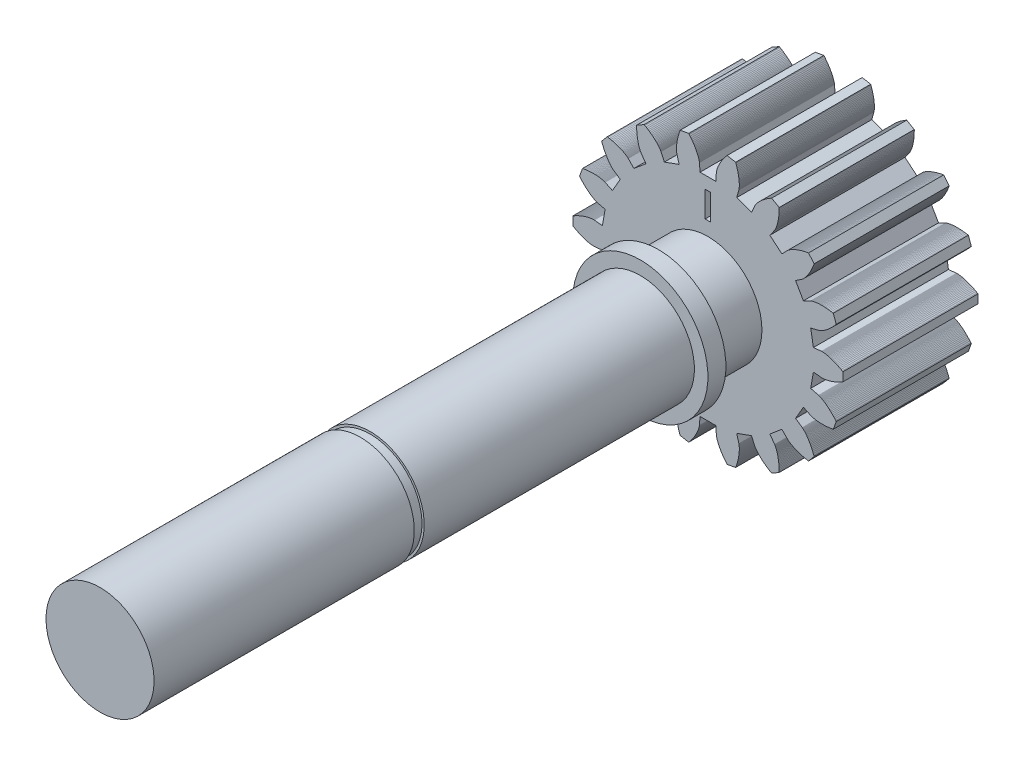
SolidWorks part; units mm, degrees
material "1.6587 (18CrNiMo7-6)"
ref_plane "Front Plane" through (0, 0, 0) normal (0, 0, 1) x (1, 0, 0)
ref_plane "Top Plane" through (0, 0, 0) normal (0, 1, 0) x (1, 0, 0)
ref_plane "Right Plane" through (0, 0, 0) normal (1, 0, 0) x (0, 0, -1)
sketch "SK_Sun_Root_Blank" plane through (0, 0, 0) normal (0, 0, 1) x (1, 0, 0)
  circle A0 centre (0, 0) radius 11.625
  dimension "D1" = 23.25
extrude "EX_Sun_Root_Blank" [suppressed] add sketch "SK_Sun_Root_Blank" along normal mid plane 15
sketch "SK_Sun_Gear_Profile_DXF" plane through (0, 0, 0) normal (0, 0, 1) x (1, 0, 0)
  line L0 (11.7158, -1.1788) -> (12.624, -1.2702)
  line L1 (12.624, -1.2702) -> (12.6307, -1.2707)
  line L2 (12.6307, -1.2707) -> (12.6421, -1.2713)
  line L3 (12.6421, -1.2713) -> (12.6583, -1.2718)
  line L4 (12.6583, -1.2718) -> (12.6793, -1.2721)
  line L5 (12.6793, -1.2721) -> (12.7051, -1.272)
  line L6 (12.7051, -1.272) -> (12.7356, -1.2713)
  line L7 (12.7356, -1.2713) -> (12.7709, -1.2697)
  line L8 (12.7709, -1.2697) -> (12.8109, -1.2672)
  line L9 (12.8109, -1.2672) -> (12.8556, -1.2635)
  line L10 (12.8556, -1.2635) -> (12.9049, -1.2585)
  line L11 (12.9049, -1.2585) -> (12.9589, -1.2519)
  line L12 (12.9589, -1.2519) -> (13.0175, -1.2437)
  line L13 (13.0175, -1.2437) -> (13.0806, -1.2335)
  line L14 (13.0806, -1.2335) -> (13.1482, -1.2213)
  line L15 (13.1482, -1.2213) -> (13.2202, -1.2068)
  line L16 (13.2202, -1.2068) -> (13.2966, -1.1899)
  line L17 (13.2966, -1.1899) -> (13.3773, -1.1704)
  line L18 (13.3773, -1.1704) -> (13.4622, -1.1481)
  line L19 (13.4622, -1.1481) -> (13.5513, -1.1229)
  line L20 (13.5513, -1.1229) -> (13.6444, -1.0945)
  line L21 (13.6444, -1.0945) -> (13.7415, -1.0629)
  line L22 (13.7415, -1.0629) -> (13.8424, -1.0279)
  line L23 (13.8424, -1.0279) -> (13.9471, -0.9892)
  line L24 (13.9471, -0.9892) -> (14.0555, -0.9468)
  line L25 (14.0555, -0.9468) -> (14.1675, -0.9005)
  line L26 (14.1675, -0.9005) -> (14.2829, -0.8501)
  line L27 (14.2829, -0.8501) -> (14.4017, -0.7954)
  line L28 (14.4017, -0.7954) -> (14.5237, -0.7364)
  line L29 (14.5237, -0.7364) -> (14.6487, -0.6729)
  line L30 (14.6487, -0.6729) -> (14.7767, -0.6048)
  line L31 (14.7767, -0.6048) -> (14.9076, -0.5318)
  line L32 (14.9076, -0.5318) -> (14.974, -0.4935)
  line L33 (14.974, -0.4935) -> (14.9907, -0.4837)
  line L34 (14.9907, -0.4837) -> (14.9917, -0.4831)
  line L35 (14.9917, -0.4831) -> (14.992, -0.4829)
  line L36 (14.992, -0.4829) -> (14.9922, -0.4828)
  line L37 (14.9922, -0.4828) -> (14.9922, 0.4828)
  line L38 (14.9922, 0.4828) -> (14.992, 0.4829)
  line L39 (14.992, 0.4829) -> (14.9917, 0.4831)
  line L40 (14.9917, 0.4831) -> (14.9907, 0.4837)
  line L41 (14.9907, 0.4837) -> (14.974, 0.4935)
  line L42 (14.974, 0.4935) -> (14.9076, 0.5318)
  line L43 (14.9076, 0.5318) -> (14.7767, 0.6048)
  line L44 (14.7767, 0.6048) -> (14.6487, 0.6729)
  line L45 (14.6487, 0.6729) -> (14.5237, 0.7364)
  line L46 (14.5237, 0.7364) -> (14.4017, 0.7954)
  line L47 (14.4017, 0.7954) -> (14.2829, 0.8501)
  line L48 (14.2829, 0.8501) -> (14.1675, 0.9005)
  line L49 (14.1675, 0.9005) -> (14.0555, 0.9468)
  line L50 (14.0555, 0.9468) -> (13.9471, 0.9892)
  line L51 (13.9471, 0.9892) -> (13.8424, 1.0279)
  line L52 (13.8424, 1.0279) -> (13.7415, 1.0629)
  line L53 (13.7415, 1.0629) -> (13.6444, 1.0945)
  line L54 (13.6444, 1.0945) -> (13.5513, 1.1229)
  line L55 (13.5513, 1.1229) -> (13.4622, 1.1481)
  line L56 (13.4622, 1.1481) -> (13.3773, 1.1704)
  line L57 (13.3773, 1.1704) -> (13.2966, 1.1899)
  line L58 (13.2966, 1.1899) -> (13.2202, 1.2068)
  line L59 (13.2202, 1.2068) -> (13.1482, 1.2213)
  line L60 (13.1482, 1.2213) -> (13.0806, 1.2335)
  line L61 (13.0806, 1.2335) -> (13.0175, 1.2437)
  line L62 (13.0175, 1.2437) -> (12.9589, 1.2519)
  line L63 (12.9589, 1.2519) -> (12.9049, 1.2585)
  line L64 (12.9049, 1.2585) -> (12.8556, 1.2635)
  line L65 (12.8556, 1.2635) -> (12.8109, 1.2672)
  line L66 (12.8109, 1.2672) -> (12.7709, 1.2697)
  line L67 (12.7709, 1.2697) -> (12.7356, 1.2713)
  line L68 (12.7356, 1.2713) -> (12.7051, 1.272)
  line L69 (12.7051, 1.272) -> (12.6793, 1.2721)
  line L70 (12.6793, 1.2721) -> (12.6583, 1.2718)
  line L71 (12.6583, 1.2718) -> (12.6421, 1.2713)
  line L72 (12.6421, 1.2713) -> (12.6307, 1.2707)
  line L73 (12.6307, 1.2707) -> (12.624, 1.2702)
  line L74 (12.624, 1.2702) -> (11.7158, 1.1788)
  line L75 (11.7158, 1.1788) -> (11.4125, 2.8993)
  line L76 (11.4125, 2.8993) -> (12.2971, 3.1241)
  line L77 (12.2971, 3.1241) -> (12.3036, 3.1259)
  line L78 (12.3036, 3.1259) -> (12.3145, 3.1293)
  line L79 (12.3145, 3.1293) -> (12.3299, 3.1343)
  line L80 (12.3299, 3.1343) -> (12.3498, 3.1412)
  line L81 (12.3498, 3.1412) -> (12.3739, 3.1501)
  line L82 (12.3739, 3.1501) -> (12.4024, 3.1612)
  line L83 (12.4024, 3.1612) -> (12.435, 3.1747)
  line L84 (12.435, 3.1747) -> (12.4717, 3.1908)
  line L85 (12.4717, 3.1908) -> (12.5125, 3.2095)
  line L86 (12.5125, 3.2095) -> (12.5571, 3.2311)
  line L87 (12.5571, 3.2311) -> (12.6056, 3.2558)
  line L88 (12.6056, 3.2558) -> (12.6578, 3.2836)
  line L89 (12.6578, 3.2836) -> (12.7136, 3.3147)
  line L90 (12.7136, 3.3147) -> (12.773, 3.3493)
  line L91 (12.773, 3.3493) -> (12.8357, 3.3876)
  line L92 (12.8357, 3.3876) -> (12.9017, 3.4296)
  line L93 (12.9017, 3.4296) -> (12.9709, 3.4755)
  line L94 (12.9709, 3.4755) -> (13.043, 3.5255)
  line L95 (13.043, 3.5255) -> (13.1181, 3.5797)
  line L96 (13.1181, 3.5797) -> (13.1959, 3.6381)
  line L97 (13.1959, 3.6381) -> (13.2763, 3.701)
  line L98 (13.2763, 3.701) -> (13.3592, 3.7685)
  line L99 (13.3592, 3.7685) -> (13.4444, 3.8406)
  line L100 (13.4444, 3.8406) -> (13.5317, 3.9176)
  line L101 (13.5317, 3.9176) -> (13.6211, 3.9994)
  line L102 (13.6211, 3.9994) -> (13.7123, 4.0863)
  line L103 (13.7123, 4.0863) -> (13.8052, 4.1782)
  line L104 (13.8052, 4.1782) -> (13.8996, 4.2754)
  line L105 (13.8996, 4.2754) -> (13.9954, 4.3778)
  line L106 (13.9954, 4.3778) -> (14.0924, 4.4856)
  line L107 (14.0924, 4.4856) -> (14.1904, 4.599)
  line L108 (14.1904, 4.599) -> (14.2397, 4.6577)
  line L109 (14.2397, 4.6577) -> (14.2521, 4.6726)
  line L110 (14.2521, 4.6726) -> (14.2529, 4.6735)
  line L111 (14.2529, 4.6735) -> (14.253, 4.6738)
  line L112 (14.253, 4.6738) -> (14.2532, 4.674)
  line L113 (14.2532, 4.674) -> (13.923, 5.5813)
  line L114 (13.923, 5.5813) -> (13.9227, 5.5814)
  line L115 (13.9227, 5.5814) -> (13.9224, 5.5814)
  line L116 (13.9224, 5.5814) -> (13.9212, 5.5817)
  line L117 (13.9212, 5.5817) -> (13.9022, 5.5851)
  line L118 (13.9022, 5.5851) -> (13.8266, 5.5984)
  line L119 (13.8266, 5.5984) -> (13.6787, 5.6222)
  line L120 (13.6787, 5.6222) -> (13.5351, 5.6425)
  line L121 (13.5351, 5.6425) -> (13.3959, 5.6594)
  line L122 (13.3959, 5.6594) -> (13.2611, 5.6731)
  line L123 (13.2611, 5.6731) -> (13.1308, 5.6838)
  line L124 (13.1308, 5.6838) -> (13.0051, 5.6917)
  line L125 (13.0051, 5.6917) -> (12.8841, 5.697)
  line L126 (12.8841, 5.697) -> (12.7677, 5.6998)
  line L127 (12.7677, 5.6998) -> (12.6561, 5.7003)
  line L128 (12.6561, 5.7003) -> (12.5492, 5.6987)
  line L129 (12.5492, 5.6987) -> (12.4472, 5.6952)
  line L130 (12.4472, 5.6952) -> (12.35, 5.69)
  line L131 (12.35, 5.69) -> (12.2577, 5.6832)
  line L132 (12.2577, 5.6832) -> (12.1703, 5.6751)
  line L133 (12.1703, 5.6751) -> (12.0878, 5.6658)
  line L134 (12.0878, 5.6658) -> (12.0102, 5.6556)
  line L135 (12.0102, 5.6556) -> (11.9376, 5.6446)
  line L136 (11.9376, 5.6446) -> (11.8699, 5.633)
  line L137 (11.8699, 5.633) -> (11.8071, 5.6209)
  line L138 (11.8071, 5.6209) -> (11.7492, 5.6087)
  line L139 (11.7492, 5.6087) -> (11.6962, 5.5964)
  line L140 (11.6962, 5.5964) -> (11.6481, 5.5842)
  line L141 (11.6481, 5.5842) -> (11.6049, 5.5724)
  line L142 (11.6049, 5.5724) -> (11.5664, 5.5611)
  line L143 (11.5664, 5.5611) -> (11.5328, 5.5504)
  line L144 (11.5328, 5.5504) -> (11.5038, 5.5407)
  line L145 (11.5038, 5.5407) -> (11.4796, 5.532)
  line L146 (11.4796, 5.532) -> (11.46, 5.5245)
  line L147 (11.46, 5.5245) -> (11.4449, 5.5185)
  line L148 (11.4449, 5.5185) -> (11.4344, 5.514)
  line L149 (11.4344, 5.514) -> (11.4283, 5.5113)
  line L150 (11.4283, 5.5113) -> (10.6061, 5.1148)
  line L151 (10.6061, 5.1148) -> (9.7326, 6.6278)
  line L152 (9.7326, 6.6278) -> (10.487, 7.1416)
  line L153 (10.487, 7.1416) -> (10.4924, 7.1455)
  line L154 (10.4924, 7.1455) -> (10.5016, 7.1524)
  line L155 (10.5016, 7.1524) -> (10.5144, 7.1624)
  line L156 (10.5144, 7.1624) -> (10.5306, 7.1756)
  line L157 (10.5306, 7.1756) -> (10.5503, 7.1923)
  line L158 (10.5503, 7.1923) -> (10.5732, 7.2125)
  line L159 (10.5732, 7.2125) -> (10.5992, 7.2363)
  line L160 (10.5992, 7.2363) -> (10.6283, 7.2639)
  line L161 (10.6283, 7.2639) -> (10.6601, 7.2955)
  line L162 (10.6601, 7.2955) -> (10.6947, 7.3311)
  line L163 (10.6947, 7.3311) -> (10.7319, 7.3708)
  line L164 (10.7319, 7.3708) -> (10.7714, 7.4148)
  line L165 (10.7714, 7.4148) -> (10.8132, 7.4631)
  line L166 (10.8132, 7.4631) -> (10.8571, 7.516)
  line L167 (10.8571, 7.516) -> (10.903, 7.5734)
  line L168 (10.903, 7.5734) -> (10.9506, 7.6354)
  line L169 (10.9506, 7.6354) -> (10.9999, 7.7022)
  line L170 (10.9999, 7.7022) -> (11.0506, 7.7739)
  line L171 (11.0506, 7.7739) -> (11.1026, 7.8504)
  line L172 (11.1026, 7.8504) -> (11.1558, 7.932)
  line L173 (11.1558, 7.932) -> (11.2098, 8.0186)
  line L174 (11.2098, 8.0186) -> (11.2646, 8.1103)
  line L175 (11.2646, 8.1103) -> (11.32, 8.2073)
  line L176 (11.32, 8.2073) -> (11.3758, 8.3094)
  line L177 (11.3758, 8.3094) -> (11.4317, 8.4169)
  line L178 (11.4317, 8.4169) -> (11.4878, 8.5297)
  line L179 (11.4878, 8.5297) -> (11.5436, 8.6479)
  line L180 (11.5436, 8.6479) -> (11.5991, 8.7715)
  line L181 (11.5991, 8.7715) -> (11.6541, 8.9005)
  line L182 (11.6541, 8.9005) -> (11.7084, 9.035)
  line L183 (11.7084, 9.035) -> (11.7617, 9.175)
  line L184 (11.7617, 9.175) -> (11.7879, 9.2471)
  line L185 (11.7879, 9.2471) -> (11.7945, 9.2653)
  line L186 (11.7945, 9.2653) -> (11.7949, 9.2664)
  line L187 (11.7949, 9.2664) -> (11.795, 9.2667)
  line L188 (11.795, 9.2667) -> (11.795, 9.267)
  line L189 (11.795, 9.267) -> (11.1744, 10.0067)
  line L190 (11.1744, 10.0067) -> (11.1741, 10.0066)
  line L191 (11.1741, 10.0066) -> (11.1738, 10.0066)
  line L192 (11.1738, 10.0066) -> (11.1726, 10.0064)
  line L193 (11.1726, 10.0064) -> (11.1535, 10.0031)
  line L194 (11.1535, 10.0031) -> (11.078, 9.9898)
  line L195 (11.078, 9.9898) -> (10.9309, 9.9616)
  line L196 (10.9309, 9.9616) -> (10.789, 9.9315)
  line L197 (10.789, 9.9315) -> (10.6524, 9.8998)
  line L198 (10.6524, 9.8998) -> (10.521, 9.8666)
  line L199 (10.521, 9.8666) -> (10.395, 9.8321)
  line L200 (10.395, 9.8321) -> (10.2741, 9.7965)
  line L201 (10.2741, 9.7965) -> (10.1586, 9.76)
  line L202 (10.1586, 9.76) -> (10.0483, 9.7228)
  line L203 (10.0483, 9.7228) -> (9.9432, 9.6851)
  line L204 (9.9432, 9.6851) -> (9.8433, 9.6471)
  line L205 (9.8433, 9.6471) -> (9.7487, 9.6089)
  line L206 (9.7487, 9.6089) -> (9.6591, 9.5708)
  line L207 (9.6591, 9.5708) -> (9.5747, 9.5328)
  line L208 (9.5747, 9.5328) -> (9.4953, 9.4953)
  line L209 (9.4953, 9.4953) -> (9.421, 9.4584)
  line L210 (9.421, 9.4584) -> (9.3516, 9.4223)
  line L211 (9.3516, 9.4223) -> (9.2871, 9.3871)
  line L212 (9.2871, 9.3871) -> (9.2275, 9.353)
  line L213 (9.2275, 9.353) -> (9.1726, 9.3202)
  line L214 (9.1726, 9.3202) -> (9.1224, 9.2889)
  line L215 (9.1224, 9.2889) -> (9.0768, 9.2592)
  line L216 (9.0768, 9.2592) -> (9.0358, 9.2313)
  line L217 (9.0358, 9.2313) -> (8.9992, 9.2054)
  line L218 (8.9992, 9.2054) -> (8.9669, 9.1816)
  line L219 (8.9669, 9.1816) -> (8.9389, 9.1601)
  line L220 (8.9389, 9.1601) -> (8.915, 9.1411)
  line L221 (8.915, 9.1411) -> (8.8952, 9.1246)
  line L222 (8.8952, 9.1246) -> (8.8793, 9.1109)
  line L223 (8.8793, 9.1109) -> (8.8673, 9.1001)
  line L224 (8.8673, 9.1001) -> (8.8589, 9.0922)
  line L225 (8.8589, 9.0922) -> (8.8541, 9.0876)
  line L226 (8.8541, 9.0876) -> (8.2171, 8.4338)
  line L227 (8.2171, 8.4338) -> (6.8788, 9.5568)
  line L228 (6.8788, 9.5568) -> (7.412, 10.2977)
  line L229 (7.412, 10.2977) -> (7.4158, 10.3032)
  line L230 (7.4158, 10.3032) -> (7.422, 10.3128)
  line L231 (7.422, 10.3128) -> (7.4306, 10.3265)
  line L232 (7.4306, 10.3265) -> (7.4414, 10.3446)
  line L233 (7.4414, 10.3446) -> (7.4541, 10.3669)
  line L234 (7.4541, 10.3669) -> (7.4688, 10.3937)
  line L235 (7.4688, 10.3937) -> (7.4851, 10.4251)
  line L236 (7.4851, 10.4251) -> (7.5029, 10.4609)
  line L237 (7.5029, 10.4609) -> (7.522, 10.5015)
  line L238 (7.522, 10.5015) -> (7.5424, 10.5468)
  line L239 (7.5424, 10.5468) -> (7.5637, 10.5968)
  line L240 (7.5637, 10.5968) -> (7.5858, 10.6517)
  line L241 (7.5858, 10.6517) -> (7.6086, 10.7114)
  line L242 (7.6086, 10.7114) -> (7.6318, 10.7761)
  line L243 (7.6318, 10.7761) -> (7.6552, 10.8457)
  line L244 (7.6552, 10.8457) -> (7.6788, 10.9203)
  line L245 (7.6788, 10.9203) -> (7.7022, 10.9999)
  line L246 (7.7022, 10.9999) -> (7.7254, 11.0846)
  line L247 (7.7254, 11.0846) -> (7.7481, 11.1743)
  line L248 (7.7481, 11.1743) -> (7.7701, 11.2691)
  line L249 (7.7701, 11.2691) -> (7.7912, 11.369)
  line L250 (7.7912, 11.369) -> (7.8114, 11.4739)
  line L251 (7.8114, 11.4739) -> (7.8303, 11.584)
  line L252 (7.8303, 11.584) -> (7.8477, 11.6991)
  line L253 (7.8477, 11.6991) -> (7.8636, 11.8192)
  line L254 (7.8636, 11.8192) -> (7.8776, 11.9444)
  line L255 (7.8776, 11.9444) -> (7.8897, 12.0745)
  line L256 (7.8897, 12.0745) -> (7.8996, 12.2096)
  line L257 (7.8996, 12.2096) -> (7.9071, 12.3497)
  line L258 (7.9071, 12.3497) -> (7.9121, 12.4946)
  line L259 (7.9121, 12.4946) -> (7.9143, 12.6444)
  line L260 (7.9143, 12.6444) -> (7.9144, 12.7211)
  line L261 (7.9144, 12.7211) -> (7.9142, 12.7405)
  line L262 (7.9142, 12.7405) -> (7.9142, 12.7417)
  line L263 (7.9142, 12.7417) -> (7.9142, 12.742)
  line L264 (7.9142, 12.742) -> (7.9142, 12.7423)
  line L265 (7.9142, 12.7423) -> (7.078, 13.225)
  line L266 (7.078, 13.225) -> (7.0778, 13.2249)
  line L267 (7.0778, 13.2249) -> (7.0775, 13.2248)
  line L268 (7.0775, 13.2248) -> (7.0764, 13.2242)
  line L269 (7.0764, 13.2242) -> (7.0596, 13.2146)
  line L270 (7.0596, 13.2146) -> (6.9932, 13.1762)
  line L271 (6.9932, 13.1762) -> (6.8646, 13.0994)
  line L272 (6.8646, 13.0994) -> (6.7416, 13.0226)
  line L273 (6.7416, 13.0226) -> (6.6241, 12.9461)
  line L274 (6.6241, 12.9461) -> (6.512, 12.8699)
  line L275 (6.512, 12.8699) -> (6.4053, 12.7944)
  line L276 (6.4053, 12.7944) -> (6.3039, 12.7197)
  line L277 (6.3039, 12.7197) -> (6.2078, 12.6459)
  line L278 (6.2078, 12.6459) -> (6.1169, 12.5732)
  line L279 (6.1169, 12.5732) -> (6.031, 12.5018)
  line L280 (6.031, 12.5018) -> (5.9502, 12.4319)
  line L281 (5.9502, 12.4319) -> (5.8743, 12.3636)
  line L282 (5.8743, 12.3636) -> (5.8032, 12.2972)
  line L283 (5.8032, 12.2972) -> (5.7368, 12.2327)
  line L284 (5.7368, 12.2327) -> (5.6751, 12.1703)
  line L285 (5.6751, 12.1703) -> (5.6179, 12.1102)
  line L286 (5.6179, 12.1102) -> (5.565, 12.0525)
  line L287 (5.565, 12.0525) -> (5.5165, 11.9973)
  line L288 (5.5165, 11.9973) -> (5.4721, 11.9449)
  line L289 (5.4721, 11.9449) -> (5.4317, 11.8953)
  line L290 (5.4317, 11.8953) -> (5.3952, 11.8487)
  line L291 (5.3952, 11.8487) -> (5.3626, 11.8053)
  line L292 (5.3626, 11.8053) -> (5.3335, 11.765)
  line L293 (5.3335, 11.765) -> (5.308, 11.7282)
  line L294 (5.308, 11.7282) -> (5.2858, 11.6948)
  line L295 (5.2858, 11.6948) -> (5.2669, 11.665)
  line L296 (5.2669, 11.665) -> (5.251, 11.6389)
  line L297 (5.251, 11.6389) -> (5.238, 11.6167)
  line L298 (5.238, 11.6167) -> (5.2277, 11.5984)
  line L299 (5.2277, 11.5984) -> (5.2201, 11.584)
  line L300 (5.2201, 11.584) -> (5.2149, 11.5738)
  line L301 (5.2149, 11.5738) -> (5.212, 11.5678)
  line L302 (5.212, 11.5678) -> (4.837, 10.7356)
  line L303 (4.837, 10.7356) -> (3.1953, 11.3332)
  line L304 (3.1953, 11.3332) -> (3.443, 12.2117)
  line L305 (3.443, 12.2117) -> (3.4447, 12.2182)
  line L306 (3.4447, 12.2182) -> (3.4472, 12.2293)
  line L307 (3.4472, 12.2293) -> (3.4506, 12.2452)
  line L308 (3.4506, 12.2452) -> (3.4545, 12.2658)
  line L309 (3.4545, 12.2658) -> (3.4589, 12.2912)
  line L310 (3.4589, 12.2912) -> (3.4635, 12.3214)
  line L311 (3.4635, 12.3214) -> (3.4681, 12.3564)
  line L312 (3.4681, 12.3564) -> (3.4726, 12.3962)
  line L313 (3.4726, 12.3962) -> (3.4767, 12.4409)
  line L314 (3.4767, 12.4409) -> (3.4803, 12.4903)
  line L315 (3.4803, 12.4903) -> (3.4832, 12.5447)
  line L316 (3.4832, 12.5447) -> (3.4852, 12.6038)
  line L317 (3.4852, 12.6038) -> (3.4862, 12.6677)
  line L318 (3.4862, 12.6677) -> (3.4859, 12.7364)
  line L319 (3.4859, 12.7364) -> (3.4841, 12.8098)
  line L320 (3.4841, 12.8098) -> (3.4807, 12.888)
  line L321 (3.4807, 12.888) -> (3.4755, 12.9709)
  line L322 (3.4755, 12.9709) -> (3.4683, 13.0583)
  line L323 (3.4683, 13.0583) -> (3.459, 13.1504)
  line L324 (3.459, 13.1504) -> (3.4472, 13.247)
  line L325 (3.4472, 13.247) -> (3.4329, 13.3481)
  line L326 (3.4329, 13.3481) -> (3.416, 13.4536)
  line L327 (3.416, 13.4536) -> (3.3961, 13.5635)
  line L328 (3.3961, 13.5635) -> (3.3731, 13.6776)
  line L329 (3.3731, 13.6776) -> (3.3469, 13.7959)
  line L330 (3.3469, 13.7959) -> (3.3173, 13.9183)
  line L331 (3.3173, 13.9183) -> (3.2842, 14.0448)
  line L332 (3.2842, 14.0448) -> (3.2473, 14.1751)
  line L333 (3.2473, 14.1751) -> (3.2064, 14.3093)
  line L334 (3.2064, 14.3093) -> (3.1615, 14.4472)
  line L335 (3.1615, 14.4472) -> (3.1124, 14.5887)
  line L336 (3.1124, 14.5887) -> (3.0862, 14.6608)
  line L337 (3.0862, 14.6608) -> (3.0795, 14.679)
  line L338 (3.0795, 14.679) -> (3.079, 14.6801)
  line L339 (3.079, 14.6801) -> (3.0789, 14.6804)
  line L340 (3.0789, 14.6804) -> (3.0788, 14.6806)
  line L341 (3.0788, 14.6806) -> (2.1279, 14.8483)
  line L342 (2.1279, 14.8483) -> (2.1277, 14.8481)
  line L343 (2.1277, 14.8481) -> (2.1275, 14.8479)
  line L344 (2.1275, 14.8479) -> (2.1267, 14.8469)
  line L345 (2.1267, 14.8469) -> (2.1142, 14.8322)
  line L346 (2.1142, 14.8322) -> (2.0649, 14.7734)
  line L347 (2.0649, 14.7734) -> (1.9704, 14.6572)
  line L348 (1.9704, 14.6572) -> (1.881, 14.543)
  line L349 (1.881, 14.543) -> (1.7968, 14.4309)
  line L350 (1.7968, 14.4309) -> (1.7175, 14.321)
  line L351 (1.7175, 14.321) -> (1.6431, 14.2136)
  line L352 (1.6431, 14.2136) -> (1.5734, 14.1086)
  line L353 (1.5734, 14.1086) -> (1.5083, 14.0064)
  line L354 (1.5083, 14.0064) -> (1.4477, 13.907)
  line L355 (1.4477, 13.907) -> (1.3915, 13.8106)
  line L356 (1.3915, 13.8106) -> (1.3394, 13.7173)
  line L357 (1.3394, 13.7173) -> (1.2914, 13.6272)
  line L358 (1.2914, 13.6272) -> (1.2474, 13.5404)
  line L359 (1.2474, 13.5404) -> (1.207, 13.4571)
  line L360 (1.207, 13.4571) -> (1.1704, 13.3773)
  line L361 (1.1704, 13.3773) -> (1.1371, 13.3012)
  line L362 (1.1371, 13.3012) -> (1.1072, 13.229)
  line L363 (1.1072, 13.229) -> (1.0804, 13.1605)
  line L364 (1.0804, 13.1605) -> (1.0567, 13.0961)
  line L365 (1.0567, 13.0961) -> (1.0357, 13.0357)
  line L366 (1.0357, 13.0357) -> (1.0174, 12.9795)
  line L367 (1.0174, 12.9795) -> (1.0015, 12.9274)
  line L368 (1.0015, 12.9274) -> (0.988, 12.8797)
  line L369 (0.988, 12.8797) -> (0.9766, 12.8363)
  line L370 (0.9766, 12.8363) -> (0.9672, 12.7974)
  line L371 (0.9672, 12.7974) -> (0.9596, 12.7629)
  line L372 (0.9596, 12.7629) -> (0.9535, 12.733)
  line L373 (0.9535, 12.733) -> (0.9489, 12.7076)
  line L374 (0.9489, 12.7076) -> (0.9456, 12.6869)
  line L375 (0.9456, 12.6869) -> (0.9433, 12.6708)
  line L376 (0.9433, 12.6708) -> (0.9419, 12.6595)
  line L377 (0.9419, 12.6595) -> (0.9413, 12.6528)
  line L378 (0.9413, 12.6528) -> (0.8735, 11.7426)
  line L379 (0.8735, 11.7426) -> (-0.8735, 11.7426)
  line L380 (-0.8735, 11.7426) -> (-0.9413, 12.6528)
  line L381 (-0.9413, 12.6528) -> (-0.9419, 12.6595)
  line L382 (-0.9419, 12.6595) -> (-0.9433, 12.6708)
  line L383 (-0.9433, 12.6708) -> (-0.9456, 12.6869)
  line L384 (-0.9456, 12.6869) -> (-0.9489, 12.7076)
  line L385 (-0.9489, 12.7076) -> (-0.9535, 12.733)
  line L386 (-0.9535, 12.733) -> (-0.9596, 12.7629)
  line L387 (-0.9596, 12.7629) -> (-0.9672, 12.7974)
  line L388 (-0.9672, 12.7974) -> (-0.9766, 12.8363)
  line L389 (-0.9766, 12.8363) -> (-0.988, 12.8797)
  line L390 (-0.988, 12.8797) -> (-1.0015, 12.9274)
  line L391 (-1.0015, 12.9274) -> (-1.0174, 12.9795)
  line L392 (-1.0174, 12.9795) -> (-1.0357, 13.0357)
  line L393 (-1.0357, 13.0357) -> (-1.0567, 13.0961)
  line L394 (-1.0567, 13.0961) -> (-1.0804, 13.1605)
  line L395 (-1.0804, 13.1605) -> (-1.1072, 13.229)
  line L396 (-1.1072, 13.229) -> (-1.1371, 13.3012)
  line L397 (-1.1371, 13.3012) -> (-1.1704, 13.3773)
  line L398 (-1.1704, 13.3773) -> (-1.2071, 13.4571)
  line L399 (-1.2071, 13.4571) -> (-1.2474, 13.5404)
  line L400 (-1.2474, 13.5404) -> (-1.2914, 13.6272)
  line L401 (-1.2914, 13.6272) -> (-1.3394, 13.7173)
  line L402 (-1.3394, 13.7173) -> (-1.3915, 13.8106)
  line L403 (-1.3915, 13.8106) -> (-1.4477, 13.907)
  line L404 (-1.4477, 13.907) -> (-1.5083, 14.0064)
  line L405 (-1.5083, 14.0064) -> (-1.5734, 14.1086)
  line L406 (-1.5734, 14.1086) -> (-1.6431, 14.2136)
  line L407 (-1.6431, 14.2136) -> (-1.7175, 14.321)
  line L408 (-1.7175, 14.321) -> (-1.7968, 14.4309)
  line L409 (-1.7968, 14.4309) -> (-1.881, 14.543)
  line L410 (-1.881, 14.543) -> (-1.9704, 14.6572)
  line L411 (-1.9704, 14.6572) -> (-2.0649, 14.7734)
  line L412 (-2.0649, 14.7734) -> (-2.1142, 14.8322)
  line L413 (-2.1142, 14.8322) -> (-2.1267, 14.8469)
  line L414 (-2.1267, 14.8469) -> (-2.1275, 14.8479)
  line L415 (-2.1275, 14.8479) -> (-2.1277, 14.8481)
  line L416 (-2.1277, 14.8481) -> (-2.1279, 14.8483)
  line L417 (-2.1279, 14.8483) -> (-3.0788, 14.6806)
  line L418 (-3.0788, 14.6806) -> (-3.0789, 14.6804)
  line L419 (-3.0789, 14.6804) -> (-3.079, 14.6801)
  line L420 (-3.079, 14.6801) -> (-3.0795, 14.679)
  line L421 (-3.0795, 14.679) -> (-3.0862, 14.6608)
  line L422 (-3.0862, 14.6608) -> (-3.1124, 14.5887)
  line L423 (-3.1124, 14.5887) -> (-3.1615, 14.4472)
  line L424 (-3.1615, 14.4472) -> (-3.2064, 14.3093)
  line L425 (-3.2064, 14.3093) -> (-3.2473, 14.1751)
  line L426 (-3.2473, 14.1751) -> (-3.2842, 14.0448)
  line L427 (-3.2842, 14.0448) -> (-3.3173, 13.9183)
  line L428 (-3.3173, 13.9183) -> (-3.3469, 13.7959)
  line L429 (-3.3469, 13.7959) -> (-3.3731, 13.6776)
  line L430 (-3.3731, 13.6776) -> (-3.3961, 13.5635)
  line L431 (-3.3961, 13.5635) -> (-3.416, 13.4536)
  line L432 (-3.416, 13.4536) -> (-3.4329, 13.3481)
  line L433 (-3.4329, 13.3481) -> (-3.4472, 13.247)
  line L434 (-3.4472, 13.247) -> (-3.459, 13.1504)
  line L435 (-3.459, 13.1504) -> (-3.4683, 13.0583)
  line L436 (-3.4683, 13.0583) -> (-3.4755, 12.9709)
  line L437 (-3.4755, 12.9709) -> (-3.4807, 12.888)
  line L438 (-3.4807, 12.888) -> (-3.4841, 12.8098)
  line L439 (-3.4841, 12.8098) -> (-3.4859, 12.7364)
  line L440 (-3.4859, 12.7364) -> (-3.4862, 12.6677)
  line L441 (-3.4862, 12.6677) -> (-3.4852, 12.6038)
  line L442 (-3.4852, 12.6038) -> (-3.4832, 12.5447)
  line L443 (-3.4832, 12.5447) -> (-3.4803, 12.4903)
  line L444 (-3.4803, 12.4903) -> (-3.4767, 12.4409)
  line L445 (-3.4767, 12.4409) -> (-3.4726, 12.3962)
  line L446 (-3.4726, 12.3962) -> (-3.4681, 12.3564)
  line L447 (-3.4681, 12.3564) -> (-3.4635, 12.3214)
  line L448 (-3.4635, 12.3214) -> (-3.4589, 12.2912)
  line L449 (-3.4589, 12.2912) -> (-3.4545, 12.2658)
  line L450 (-3.4545, 12.2658) -> (-3.4506, 12.2452)
  line L451 (-3.4506, 12.2452) -> (-3.4472, 12.2293)
  line L452 (-3.4472, 12.2293) -> (-3.4447, 12.2182)
  line L453 (-3.4447, 12.2182) -> (-3.443, 12.2117)
  line L454 (-3.443, 12.2117) -> (-3.1953, 11.3332)
  line L455 (-3.1953, 11.3332) -> (-4.837, 10.7356)
  line L456 (-4.837, 10.7356) -> (-5.212, 11.5678)
  line L457 (-5.212, 11.5678) -> (-5.2149, 11.5738)
  line L458 (-5.2149, 11.5738) -> (-5.2201, 11.584)
  line L459 (-5.2201, 11.584) -> (-5.2277, 11.5984)
  line L460 (-5.2277, 11.5984) -> (-5.238, 11.6167)
  line L461 (-5.238, 11.6167) -> (-5.251, 11.6389)
  line L462 (-5.251, 11.6389) -> (-5.2669, 11.665)
  line L463 (-5.2669, 11.665) -> (-5.2858, 11.6948)
  line L464 (-5.2858, 11.6948) -> (-5.308, 11.7282)
  line L465 (-5.308, 11.7282) -> (-5.3335, 11.765)
  line L466 (-5.3335, 11.765) -> (-5.3626, 11.8053)
  line L467 (-5.3626, 11.8053) -> (-5.3952, 11.8487)
  line L468 (-5.3952, 11.8487) -> (-5.4317, 11.8953)
  line L469 (-5.4317, 11.8953) -> (-5.4721, 11.9449)
  line L470 (-5.4721, 11.9449) -> (-5.5165, 11.9973)
  line L471 (-5.5165, 11.9973) -> (-5.565, 12.0525)
  line L472 (-5.565, 12.0525) -> (-5.6179, 12.1102)
  line L473 (-5.6179, 12.1102) -> (-5.6751, 12.1703)
  line L474 (-5.6751, 12.1703) -> (-5.7368, 12.2327)
  line L475 (-5.7368, 12.2327) -> (-5.8032, 12.2972)
  line L476 (-5.8032, 12.2972) -> (-5.8743, 12.3636)
  line L477 (-5.8743, 12.3636) -> (-5.9502, 12.4319)
  line L478 (-5.9502, 12.4319) -> (-6.031, 12.5018)
  line L479 (-6.031, 12.5018) -> (-6.1169, 12.5732)
  line L480 (-6.1169, 12.5732) -> (-6.2078, 12.6459)
  line L481 (-6.2078, 12.6459) -> (-6.3039, 12.7197)
  line L482 (-6.3039, 12.7197) -> (-6.4053, 12.7944)
  line L483 (-6.4053, 12.7944) -> (-6.512, 12.8699)
  line L484 (-6.512, 12.8699) -> (-6.6241, 12.9461)
  line L485 (-6.6241, 12.9461) -> (-6.7416, 13.0226)
  line L486 (-6.7416, 13.0226) -> (-6.8646, 13.0994)
  line L487 (-6.8646, 13.0994) -> (-6.9932, 13.1762)
  line L488 (-6.9932, 13.1762) -> (-7.0596, 13.2146)
  line L489 (-7.0596, 13.2146) -> (-7.0764, 13.2242)
  line L490 (-7.0764, 13.2242) -> (-7.0775, 13.2248)
  line L491 (-7.0775, 13.2248) -> (-7.0778, 13.2249)
  line L492 (-7.0778, 13.2249) -> (-7.078, 13.225)
  line L493 (-7.078, 13.225) -> (-7.9142, 12.7423)
  line L494 (-7.9142, 12.7423) -> (-7.9142, 12.742)
  line L495 (-7.9142, 12.742) -> (-7.9142, 12.7417)
  line L496 (-7.9142, 12.7417) -> (-7.9142, 12.7405)
  line L497 (-7.9142, 12.7405) -> (-7.9144, 12.7211)
  line L498 (-7.9144, 12.7211) -> (-7.9143, 12.6444)
  line L499 (-7.9143, 12.6444) -> (-7.9121, 12.4946)
  line L500 (-7.9121, 12.4946) -> (-7.9071, 12.3497)
  line L501 (-7.9071, 12.3497) -> (-7.8996, 12.2096)
  line L502 (-7.8996, 12.2096) -> (-7.8897, 12.0745)
  line L503 (-7.8897, 12.0745) -> (-7.8776, 11.9444)
  line L504 (-7.8776, 11.9444) -> (-7.8636, 11.8192)
  line L505 (-7.8636, 11.8192) -> (-7.8477, 11.6991)
  line L506 (-7.8477, 11.6991) -> (-7.8303, 11.584)
  line L507 (-7.8303, 11.584) -> (-7.8114, 11.4739)
  line L508 (-7.8114, 11.4739) -> (-7.7912, 11.369)
  line L509 (-7.7912, 11.369) -> (-7.7701, 11.2691)
  line L510 (-7.7701, 11.2691) -> (-7.7481, 11.1743)
  line L511 (-7.7481, 11.1743) -> (-7.7254, 11.0846)
  line L512 (-7.7254, 11.0846) -> (-7.7022, 10.9999)
  line L513 (-7.7022, 10.9999) -> (-7.6788, 10.9203)
  line L514 (-7.6788, 10.9203) -> (-7.6552, 10.8457)
  line L515 (-7.6552, 10.8457) -> (-7.6318, 10.7761)
  line L516 (-7.6318, 10.7761) -> (-7.6086, 10.7114)
  line L517 (-7.6086, 10.7114) -> (-7.5858, 10.6517)
  line L518 (-7.5858, 10.6517) -> (-7.5637, 10.5968)
  line L519 (-7.5637, 10.5968) -> (-7.5424, 10.5468)
  line L520 (-7.5424, 10.5468) -> (-7.522, 10.5015)
  line L521 (-7.522, 10.5015) -> (-7.5029, 10.4609)
  line L522 (-7.5029, 10.4609) -> (-7.4851, 10.4251)
  line L523 (-7.4851, 10.4251) -> (-7.4688, 10.3937)
  line L524 (-7.4688, 10.3937) -> (-7.4541, 10.3669)
  line L525 (-7.4541, 10.3669) -> (-7.4414, 10.3446)
  line L526 (-7.4414, 10.3446) -> (-7.4306, 10.3265)
  line L527 (-7.4306, 10.3265) -> (-7.422, 10.3128)
  line L528 (-7.422, 10.3128) -> (-7.4158, 10.3032)
  line L529 (-7.4158, 10.3032) -> (-7.412, 10.2977)
  line L530 (-7.412, 10.2977) -> (-6.8788, 9.5568)
  line L531 (-6.8788, 9.5568) -> (-8.2171, 8.4338)
  line L532 (-8.2171, 8.4338) -> (-8.8541, 9.0876)
  line L533 (-8.8541, 9.0876) -> (-8.8589, 9.0922)
  line L534 (-8.8589, 9.0922) -> (-8.8673, 9.1001)
  line L535 (-8.8673, 9.1001) -> (-8.8793, 9.1109)
  line L536 (-8.8793, 9.1109) -> (-8.8952, 9.1246)
  line L537 (-8.8952, 9.1246) -> (-8.915, 9.1411)
  line L538 (-8.915, 9.1411) -> (-8.9389, 9.1601)
  line L539 (-8.9389, 9.1601) -> (-8.9669, 9.1816)
  line L540 (-8.9669, 9.1816) -> (-8.9992, 9.2054)
  line L541 (-8.9992, 9.2054) -> (-9.0358, 9.2313)
  line L542 (-9.0358, 9.2313) -> (-9.0768, 9.2592)
  line L543 (-9.0768, 9.2592) -> (-9.1224, 9.2889)
  line L544 (-9.1224, 9.2889) -> (-9.1726, 9.3202)
  line L545 (-9.1726, 9.3202) -> (-9.2275, 9.353)
  line L546 (-9.2275, 9.353) -> (-9.2871, 9.3871)
  line L547 (-9.2871, 9.3871) -> (-9.3516, 9.4223)
  line L548 (-9.3516, 9.4223) -> (-9.421, 9.4584)
  line L549 (-9.421, 9.4584) -> (-9.4953, 9.4953)
  line L550 (-9.4953, 9.4953) -> (-9.5747, 9.5328)
  line L551 (-9.5747, 9.5328) -> (-9.6591, 9.5708)
  line L552 (-9.6591, 9.5708) -> (-9.7487, 9.6089)
  line L553 (-9.7487, 9.6089) -> (-9.8433, 9.6471)
  line L554 (-9.8433, 9.6471) -> (-9.9432, 9.6851)
  line L555 (-9.9432, 9.6851) -> (-10.0483, 9.7228)
  line L556 (-10.0483, 9.7228) -> (-10.1586, 9.76)
  line L557 (-10.1586, 9.76) -> (-10.2741, 9.7965)
  line L558 (-10.2741, 9.7965) -> (-10.395, 9.8321)
  line L559 (-10.395, 9.8321) -> (-10.521, 9.8666)
  line L560 (-10.521, 9.8666) -> (-10.6524, 9.8998)
  line L561 (-10.6524, 9.8998) -> (-10.789, 9.9315)
  line L562 (-10.789, 9.9315) -> (-10.9309, 9.9616)
  line L563 (-10.9309, 9.9616) -> (-11.078, 9.9898)
  line L564 (-11.078, 9.9898) -> (-11.1535, 10.0031)
  line L565 (-11.1535, 10.0031) -> (-11.1726, 10.0064)
  line L566 (-11.1726, 10.0064) -> (-11.1738, 10.0066)
  line L567 (-11.1738, 10.0066) -> (-11.1741, 10.0066)
  line L568 (-11.1741, 10.0066) -> (-11.1744, 10.0067)
  line L569 (-11.1744, 10.0067) -> (-11.795, 9.267)
  line L570 (-11.795, 9.267) -> (-11.795, 9.2667)
  line L571 (-11.795, 9.2667) -> (-11.7949, 9.2664)
  line L572 (-11.7949, 9.2664) -> (-11.7945, 9.2653)
  line L573 (-11.7945, 9.2653) -> (-11.7879, 9.2471)
  line L574 (-11.7879, 9.2471) -> (-11.7617, 9.175)
  line L575 (-11.7617, 9.175) -> (-11.7084, 9.035)
  line L576 (-11.7084, 9.035) -> (-11.6541, 8.9005)
  line L577 (-11.6541, 8.9005) -> (-11.5991, 8.7715)
  line L578 (-11.5991, 8.7715) -> (-11.5436, 8.6479)
  line L579 (-11.5436, 8.6479) -> (-11.4878, 8.5297)
  line L580 (-11.4878, 8.5297) -> (-11.4317, 8.4169)
  line L581 (-11.4317, 8.4169) -> (-11.3758, 8.3094)
  line L582 (-11.3758, 8.3094) -> (-11.32, 8.2073)
  line L583 (-11.32, 8.2073) -> (-11.2646, 8.1103)
  line L584 (-11.2646, 8.1103) -> (-11.2098, 8.0186)
  line L585 (-11.2098, 8.0186) -> (-11.1558, 7.932)
  line L586 (-11.1558, 7.932) -> (-11.1026, 7.8504)
  line L587 (-11.1026, 7.8504) -> (-11.0506, 7.7739)
  line L588 (-11.0506, 7.7739) -> (-10.9999, 7.7022)
  line L589 (-10.9999, 7.7022) -> (-10.9506, 7.6354)
  line L590 (-10.9506, 7.6354) -> (-10.903, 7.5734)
  line L591 (-10.903, 7.5734) -> (-10.8571, 7.516)
  line L592 (-10.8571, 7.516) -> (-10.8132, 7.4631)
  line L593 (-10.8132, 7.4631) -> (-10.7714, 7.4148)
  line L594 (-10.7714, 7.4148) -> (-10.7319, 7.3708)
  line L595 (-10.7319, 7.3708) -> (-10.6947, 7.3311)
  line L596 (-10.6947, 7.3311) -> (-10.6601, 7.2955)
  line L597 (-10.6601, 7.2955) -> (-10.6283, 7.2639)
  line L598 (-10.6283, 7.2639) -> (-10.5992, 7.2363)
  line L599 (-10.5992, 7.2363) -> (-10.5732, 7.2125)
  line L600 (-10.5732, 7.2125) -> (-10.5503, 7.1923)
  line L601 (-10.5503, 7.1923) -> (-10.5306, 7.1756)
  line L602 (-10.5306, 7.1756) -> (-10.5144, 7.1624)
  line L603 (-10.5144, 7.1624) -> (-10.5016, 7.1524)
  line L604 (-10.5016, 7.1524) -> (-10.4924, 7.1455)
  line L605 (-10.4924, 7.1455) -> (-10.487, 7.1416)
  line L606 (-10.487, 7.1416) -> (-9.7326, 6.6278)
  line L607 (-9.7326, 6.6278) -> (-10.6061, 5.1148)
  line L608 (-10.6061, 5.1148) -> (-11.4283, 5.5113)
  line L609 (-11.4283, 5.5113) -> (-11.4344, 5.514)
  line L610 (-11.4344, 5.514) -> (-11.4449, 5.5185)
  line L611 (-11.4449, 5.5185) -> (-11.46, 5.5245)
  line L612 (-11.46, 5.5245) -> (-11.4796, 5.532)
  line L613 (-11.4796, 5.532) -> (-11.5038, 5.5407)
  line L614 (-11.5038, 5.5407) -> (-11.5328, 5.5504)
  line L615 (-11.5328, 5.5504) -> (-11.5664, 5.5611)
  line L616 (-11.5664, 5.5611) -> (-11.6049, 5.5724)
  line L617 (-11.6049, 5.5724) -> (-11.6481, 5.5842)
  line L618 (-11.6481, 5.5842) -> (-11.6962, 5.5964)
  line L619 (-11.6962, 5.5964) -> (-11.7492, 5.6087)
  line L620 (-11.7492, 5.6087) -> (-11.8071, 5.6209)
  line L621 (-11.8071, 5.6209) -> (-11.8699, 5.633)
  line L622 (-11.8699, 5.633) -> (-11.9376, 5.6446)
  line L623 (-11.9376, 5.6446) -> (-12.0102, 5.6556)
  line L624 (-12.0102, 5.6556) -> (-12.0878, 5.6658)
  line L625 (-12.0878, 5.6658) -> (-12.1703, 5.6751)
  line L626 (-12.1703, 5.6751) -> (-12.2577, 5.6832)
  line L627 (-12.2577, 5.6832) -> (-12.35, 5.69)
  line L628 (-12.35, 5.69) -> (-12.4472, 5.6952)
  line L629 (-12.4472, 5.6952) -> (-12.5492, 5.6987)
  line L630 (-12.5492, 5.6987) -> (-12.6561, 5.7003)
  line L631 (-12.6561, 5.7003) -> (-12.7677, 5.6998)
  line L632 (-12.7677, 5.6998) -> (-12.8841, 5.697)
  line L633 (-12.8841, 5.697) -> (-13.0051, 5.6917)
  line L634 (-13.0051, 5.6917) -> (-13.1308, 5.6838)
  line L635 (-13.1308, 5.6838) -> (-13.2611, 5.6731)
  line L636 (-13.2611, 5.6731) -> (-13.3959, 5.6594)
  line L637 (-13.3959, 5.6594) -> (-13.5351, 5.6425)
  line L638 (-13.5351, 5.6425) -> (-13.6787, 5.6222)
  line L639 (-13.6787, 5.6222) -> (-13.8266, 5.5984)
  line L640 (-13.8266, 5.5984) -> (-13.9022, 5.5851)
  line L641 (-13.9022, 5.5851) -> (-13.9212, 5.5817)
  line L642 (-13.9212, 5.5817) -> (-13.9224, 5.5814)
  line L643 (-13.9224, 5.5814) -> (-13.9227, 5.5814)
  line L644 (-13.9227, 5.5814) -> (-13.923, 5.5813)
  line L645 (-13.923, 5.5813) -> (-14.2532, 4.674)
  line L646 (-14.2532, 4.674) -> (-14.253, 4.6738)
  line L647 (-14.253, 4.6738) -> (-14.2529, 4.6735)
  line L648 (-14.2529, 4.6735) -> (-14.2521, 4.6726)
  line L649 (-14.2521, 4.6726) -> (-14.2397, 4.6577)
  line L650 (-14.2397, 4.6577) -> (-14.1904, 4.599)
  line L651 (-14.1904, 4.599) -> (-14.0924, 4.4856)
  line L652 (-14.0924, 4.4856) -> (-13.9954, 4.3778)
  line L653 (-13.9954, 4.3778) -> (-13.8996, 4.2754)
  line L654 (-13.8996, 4.2754) -> (-13.8052, 4.1782)
  line L655 (-13.8052, 4.1782) -> (-13.7123, 4.0863)
  line L656 (-13.7123, 4.0863) -> (-13.6211, 3.9994)
  line L657 (-13.6211, 3.9994) -> (-13.5317, 3.9176)
  line L658 (-13.5317, 3.9176) -> (-13.4444, 3.8406)
  line L659 (-13.4444, 3.8406) -> (-13.3592, 3.7685)
  line L660 (-13.3592, 3.7685) -> (-13.2763, 3.701)
  line L661 (-13.2763, 3.701) -> (-13.1959, 3.6381)
  line L662 (-13.1959, 3.6381) -> (-13.1181, 3.5797)
  line L663 (-13.1181, 3.5797) -> (-13.043, 3.5255)
  line L664 (-13.043, 3.5255) -> (-12.9709, 3.4755)
  line L665 (-12.9709, 3.4755) -> (-12.9017, 3.4296)
  line L666 (-12.9017, 3.4296) -> (-12.8357, 3.3876)
  line L667 (-12.8357, 3.3876) -> (-12.773, 3.3493)
  line L668 (-12.773, 3.3493) -> (-12.7136, 3.3147)
  line L669 (-12.7136, 3.3147) -> (-12.6578, 3.2836)
  line L670 (-12.6578, 3.2836) -> (-12.6056, 3.2558)
  line L671 (-12.6056, 3.2558) -> (-12.5571, 3.2311)
  line L672 (-12.5571, 3.2311) -> (-12.5125, 3.2095)
  line L673 (-12.5125, 3.2095) -> (-12.4717, 3.1908)
  line L674 (-12.4717, 3.1908) -> (-12.435, 3.1747)
  line L675 (-12.435, 3.1747) -> (-12.4024, 3.1612)
  line L676 (-12.4024, 3.1612) -> (-12.3739, 3.1501)
  line L677 (-12.3739, 3.1501) -> (-12.3498, 3.1412)
  line L678 (-12.3498, 3.1412) -> (-12.3299, 3.1343)
  line L679 (-12.3299, 3.1343) -> (-12.3145, 3.1293)
  line L680 (-12.3145, 3.1293) -> (-12.3036, 3.1259)
  line L681 (-12.3036, 3.1259) -> (-12.2971, 3.1241)
  line L682 (-12.2971, 3.1241) -> (-11.4125, 2.8993)
  line L683 (-11.4125, 2.8993) -> (-11.7158, 1.1788)
  line L684 (-11.7158, 1.1788) -> (-12.624, 1.2702)
  line L685 (-12.624, 1.2702) -> (-12.6307, 1.2707)
  line L686 (-12.6307, 1.2707) -> (-12.6421, 1.2713)
  line L687 (-12.6421, 1.2713) -> (-12.6583, 1.2718)
  line L688 (-12.6583, 1.2718) -> (-12.6793, 1.2721)
  line L689 (-12.6793, 1.2721) -> (-12.7051, 1.272)
  line L690 (-12.7051, 1.272) -> (-12.7356, 1.2713)
  line L691 (-12.7356, 1.2713) -> (-12.7709, 1.2697)
  line L692 (-12.7709, 1.2697) -> (-12.8109, 1.2672)
  line L693 (-12.8109, 1.2672) -> (-12.8556, 1.2635)
  line L694 (-12.8556, 1.2635) -> (-12.9049, 1.2585)
  line L695 (-12.9049, 1.2585) -> (-12.9589, 1.2519)
  line L696 (-12.9589, 1.2519) -> (-13.0175, 1.2437)
  line L697 (-13.0175, 1.2437) -> (-13.0806, 1.2335)
  line L698 (-13.0806, 1.2335) -> (-13.1482, 1.2213)
  line L699 (-13.1482, 1.2213) -> (-13.2202, 1.2068)
  line L700 (-13.2202, 1.2068) -> (-13.2966, 1.1899)
  line L701 (-13.2966, 1.1899) -> (-13.3773, 1.1704)
  line L702 (-13.3773, 1.1704) -> (-13.4622, 1.1481)
  line L703 (-13.4622, 1.1481) -> (-13.5513, 1.1229)
  line L704 (-13.5513, 1.1229) -> (-13.6444, 1.0945)
  line L705 (-13.6444, 1.0945) -> (-13.7415, 1.0629)
  line L706 (-13.7415, 1.0629) -> (-13.8424, 1.0279)
  line L707 (-13.8424, 1.0279) -> (-13.9471, 0.9892)
  line L708 (-13.9471, 0.9892) -> (-14.0555, 0.9468)
  line L709 (-14.0555, 0.9468) -> (-14.1675, 0.9005)
  line L710 (-14.1675, 0.9005) -> (-14.2829, 0.8501)
  line L711 (-14.2829, 0.8501) -> (-14.4017, 0.7954)
  line L712 (-14.4017, 0.7954) -> (-14.5237, 0.7364)
  line L713 (-14.5237, 0.7364) -> (-14.6487, 0.6729)
  line L714 (-14.6487, 0.6729) -> (-14.7767, 0.6048)
  line L715 (-14.7767, 0.6048) -> (-14.9076, 0.5318)
  line L716 (-14.9076, 0.5318) -> (-14.974, 0.4935)
  line L717 (-14.974, 0.4935) -> (-14.9907, 0.4837)
  line L718 (-14.9907, 0.4837) -> (-14.9917, 0.4831)
  line L719 (-14.9917, 0.4831) -> (-14.992, 0.4829)
  line L720 (-14.992, 0.4829) -> (-14.9922, 0.4828)
  line L721 (-14.9922, 0.4828) -> (-14.9922, -0.4828)
  line L722 (-14.9922, -0.4828) -> (-14.992, -0.4829)
  line L723 (-14.992, -0.4829) -> (-14.9917, -0.4831)
  line L724 (-14.9917, -0.4831) -> (-14.9907, -0.4837)
  line L725 (-14.9907, -0.4837) -> (-14.974, -0.4935)
  line L726 (-14.974, -0.4935) -> (-14.9076, -0.5318)
  line L727 (-14.9076, -0.5318) -> (-14.7767, -0.6048)
  line L728 (-14.7767, -0.6048) -> (-14.6487, -0.6729)
  line L729 (-14.6487, -0.6729) -> (-14.5237, -0.7364)
  line L730 (-14.5237, -0.7364) -> (-14.4017, -0.7954)
  line L731 (-14.4017, -0.7954) -> (-14.2829, -0.8501)
  line L732 (-14.2829, -0.8501) -> (-14.1675, -0.9005)
  line L733 (-14.1675, -0.9005) -> (-14.0555, -0.9468)
  line L734 (-14.0555, -0.9468) -> (-13.9471, -0.9892)
  line L735 (-13.9471, -0.9892) -> (-13.8424, -1.0279)
  line L736 (-13.8424, -1.0279) -> (-13.7415, -1.0629)
  line L737 (-13.7415, -1.0629) -> (-13.6444, -1.0945)
  line L738 (-13.6444, -1.0945) -> (-13.5513, -1.1229)
  line L739 (-13.5513, -1.1229) -> (-13.4622, -1.1481)
  line L740 (-13.4622, -1.1481) -> (-13.3773, -1.1704)
  line L741 (-13.3773, -1.1704) -> (-13.2966, -1.1899)
  line L742 (-13.2966, -1.1899) -> (-13.2202, -1.2068)
  line L743 (-13.2202, -1.2068) -> (-13.1482, -1.2213)
  line L744 (-13.1482, -1.2213) -> (-13.0806, -1.2335)
  line L745 (-13.0806, -1.2335) -> (-13.0175, -1.2437)
  line L746 (-13.0175, -1.2437) -> (-12.9589, -1.2519)
  line L747 (-12.9589, -1.2519) -> (-12.9049, -1.2585)
  line L748 (-12.9049, -1.2585) -> (-12.8556, -1.2635)
  line L749 (-12.8556, -1.2635) -> (-12.8109, -1.2672)
  line L750 (-12.8109, -1.2672) -> (-12.7709, -1.2697)
  line L751 (-12.7709, -1.2697) -> (-12.7356, -1.2713)
  line L752 (-12.7356, -1.2713) -> (-12.7051, -1.272)
  line L753 (-12.7051, -1.272) -> (-12.6793, -1.2721)
  line L754 (-12.6793, -1.2721) -> (-12.6583, -1.2718)
  line L755 (-12.6583, -1.2718) -> (-12.6421, -1.2713)
  line L756 (-12.6421, -1.2713) -> (-12.6307, -1.2707)
  line L757 (-12.6307, -1.2707) -> (-12.624, -1.2702)
  line L758 (-12.624, -1.2702) -> (-11.7158, -1.1788)
  line L759 (-11.7158, -1.1788) -> (-11.4125, -2.8993)
  line L760 (-11.4125, -2.8993) -> (-12.2971, -3.1241)
  line L761 (-12.2971, -3.1241) -> (-12.3036, -3.1259)
  line L762 (-12.3036, -3.1259) -> (-12.3145, -3.1293)
  line L763 (-12.3145, -3.1293) -> (-12.3299, -3.1343)
  line L764 (-12.3299, -3.1343) -> (-12.3498, -3.1412)
  line L765 (-12.3498, -3.1412) -> (-12.3739, -3.1501)
  line L766 (-12.3739, -3.1501) -> (-12.4024, -3.1612)
  line L767 (-12.4024, -3.1612) -> (-12.435, -3.1747)
  line L768 (-12.435, -3.1747) -> (-12.4717, -3.1908)
  line L769 (-12.4717, -3.1908) -> (-12.5125, -3.2095)
  line L770 (-12.5125, -3.2095) -> (-12.5571, -3.2311)
  line L771 (-12.5571, -3.2311) -> (-12.6056, -3.2558)
  line L772 (-12.6056, -3.2558) -> (-12.6578, -3.2836)
  line L773 (-12.6578, -3.2836) -> (-12.7136, -3.3147)
  line L774 (-12.7136, -3.3147) -> (-12.773, -3.3493)
  line L775 (-12.773, -3.3493) -> (-12.8357, -3.3876)
  line L776 (-12.8357, -3.3876) -> (-12.9017, -3.4296)
  line L777 (-12.9017, -3.4296) -> (-12.9709, -3.4755)
  line L778 (-12.9709, -3.4755) -> (-13.043, -3.5255)
  line L779 (-13.043, -3.5255) -> (-13.1181, -3.5797)
  line L780 (-13.1181, -3.5797) -> (-13.1959, -3.6381)
  line L781 (-13.1959, -3.6381) -> (-13.2763, -3.701)
  line L782 (-13.2763, -3.701) -> (-13.3592, -3.7685)
  line L783 (-13.3592, -3.7685) -> (-13.4444, -3.8406)
  line L784 (-13.4444, -3.8406) -> (-13.5317, -3.9176)
  line L785 (-13.5317, -3.9176) -> (-13.6211, -3.9994)
  line L786 (-13.6211, -3.9994) -> (-13.7123, -4.0863)
  line L787 (-13.7123, -4.0863) -> (-13.8052, -4.1782)
  line L788 (-13.8052, -4.1782) -> (-13.8996, -4.2754)
  line L789 (-13.8996, -4.2754) -> (-13.9954, -4.3778)
  line L790 (-13.9954, -4.3778) -> (-14.0924, -4.4856)
  line L791 (-14.0924, -4.4856) -> (-14.1904, -4.599)
  line L792 (-14.1904, -4.599) -> (-14.2397, -4.6577)
  line L793 (-14.2397, -4.6577) -> (-14.2521, -4.6726)
  line L794 (-14.2521, -4.6726) -> (-14.2529, -4.6735)
  line L795 (-14.2529, -4.6735) -> (-14.253, -4.6738)
  line L796 (-14.253, -4.6738) -> (-14.2532, -4.674)
  line L797 (-14.2532, -4.674) -> (-13.923, -5.5813)
  line L798 (-13.923, -5.5813) -> (-13.9227, -5.5814)
  line L799 (-13.9227, -5.5814) -> (-13.9224, -5.5814)
  line L800 (-13.9224, -5.5814) -> (-13.9212, -5.5817)
  line L801 (-13.9212, -5.5817) -> (-13.9022, -5.5851)
  line L802 (-13.9022, -5.5851) -> (-13.8266, -5.5984)
  line L803 (-13.8266, -5.5984) -> (-13.6787, -5.6222)
  line L804 (-13.6787, -5.6222) -> (-13.5351, -5.6425)
  line L805 (-13.5351, -5.6425) -> (-13.3959, -5.6594)
  line L806 (-13.3959, -5.6594) -> (-13.2611, -5.6731)
  line L807 (-13.2611, -5.6731) -> (-13.1308, -5.6838)
  line L808 (-13.1308, -5.6838) -> (-13.0051, -5.6917)
  line L809 (-13.0051, -5.6917) -> (-12.8841, -5.697)
  line L810 (-12.8841, -5.697) -> (-12.7677, -5.6998)
  line L811 (-12.7677, -5.6998) -> (-12.6561, -5.7003)
  line L812 (-12.6561, -5.7003) -> (-12.5492, -5.6987)
  line L813 (-12.5492, -5.6987) -> (-12.4472, -5.6952)
  line L814 (-12.4472, -5.6952) -> (-12.35, -5.69)
  line L815 (-12.35, -5.69) -> (-12.2577, -5.6832)
  line L816 (-12.2577, -5.6832) -> (-12.1703, -5.6751)
  line L817 (-12.1703, -5.6751) -> (-12.0878, -5.6658)
  line L818 (-12.0878, -5.6658) -> (-12.0102, -5.6556)
  line L819 (-12.0102, -5.6556) -> (-11.9376, -5.6446)
  line L820 (-11.9376, -5.6446) -> (-11.8699, -5.633)
  line L821 (-11.8699, -5.633) -> (-11.8071, -5.6209)
  line L822 (-11.8071, -5.6209) -> (-11.7492, -5.6087)
  line L823 (-11.7492, -5.6087) -> (-11.6962, -5.5964)
  line L824 (-11.6962, -5.5964) -> (-11.6481, -5.5842)
  line L825 (-11.6481, -5.5842) -> (-11.6049, -5.5724)
  line L826 (-11.6049, -5.5724) -> (-11.5664, -5.5611)
  line L827 (-11.5664, -5.5611) -> (-11.5328, -5.5504)
  line L828 (-11.5328, -5.5504) -> (-11.5038, -5.5407)
  line L829 (-11.5038, -5.5407) -> (-11.4796, -5.532)
  line L830 (-11.4796, -5.532) -> (-11.46, -5.5245)
  line L831 (-11.46, -5.5245) -> (-11.4449, -5.5185)
  line L832 (-11.4449, -5.5185) -> (-11.4344, -5.514)
  line L833 (-11.4344, -5.514) -> (-11.4283, -5.5113)
  line L834 (-11.4283, -5.5113) -> (-10.6061, -5.1148)
  line L835 (-10.6061, -5.1148) -> (-9.7326, -6.6278)
  line L836 (-9.7326, -6.6278) -> (-10.487, -7.1416)
  line L837 (-10.487, -7.1416) -> (-10.4924, -7.1455)
  line L838 (-10.4924, -7.1455) -> (-10.5016, -7.1524)
  line L839 (-10.5016, -7.1524) -> (-10.5144, -7.1624)
  line L840 (-10.5144, -7.1624) -> (-10.5306, -7.1756)
  line L841 (-10.5306, -7.1756) -> (-10.5503, -7.1923)
  line L842 (-10.5503, -7.1923) -> (-10.5732, -7.2125)
  line L843 (-10.5732, -7.2125) -> (-10.5992, -7.2363)
  line L844 (-10.5992, -7.2363) -> (-10.6283, -7.2639)
  line L845 (-10.6283, -7.2639) -> (-10.6601, -7.2955)
  line L846 (-10.6601, -7.2955) -> (-10.6947, -7.3311)
  line L847 (-10.6947, -7.3311) -> (-10.7319, -7.3708)
  line L848 (-10.7319, -7.3708) -> (-10.7714, -7.4148)
  line L849 (-10.7714, -7.4148) -> (-10.8132, -7.4631)
  line L850 (-10.8132, -7.4631) -> (-10.8571, -7.516)
  line L851 (-10.8571, -7.516) -> (-10.903, -7.5734)
  line L852 (-10.903, -7.5734) -> (-10.9506, -7.6354)
  line L853 (-10.9506, -7.6354) -> (-10.9999, -7.7022)
  line L854 (-10.9999, -7.7022) -> (-11.0506, -7.7739)
  line L855 (-11.0506, -7.7739) -> (-11.1026, -7.8504)
  line L856 (-11.1026, -7.8504) -> (-11.1558, -7.932)
  line L857 (-11.1558, -7.932) -> (-11.2098, -8.0186)
  line L858 (-11.2098, -8.0186) -> (-11.2646, -8.1103)
  line L859 (-11.2646, -8.1103) -> (-11.32, -8.2073)
  line L860 (-11.32, -8.2073) -> (-11.3758, -8.3094)
  line L861 (-11.3758, -8.3094) -> (-11.4317, -8.4169)
  line L862 (-11.4317, -8.4169) -> (-11.4878, -8.5297)
  line L863 (-11.4878, -8.5297) -> (-11.5436, -8.6479)
  line L864 (-11.5436, -8.6479) -> (-11.5991, -8.7715)
  line L865 (-11.5991, -8.7715) -> (-11.6541, -8.9005)
  line L866 (-11.6541, -8.9005) -> (-11.7084, -9.035)
  line L867 (-11.7084, -9.035) -> (-11.7617, -9.175)
  line L868 (-11.7617, -9.175) -> (-11.7879, -9.2471)
  line L869 (-11.7879, -9.2471) -> (-11.7945, -9.2653)
  line L870 (-11.7945, -9.2653) -> (-11.7949, -9.2664)
  line L871 (-11.7949, -9.2664) -> (-11.795, -9.2667)
  line L872 (-11.795, -9.2667) -> (-11.795, -9.267)
  line L873 (-11.795, -9.267) -> (-11.1744, -10.0067)
  line L874 (-11.1744, -10.0067) -> (-11.1741, -10.0066)
  line L875 (-11.1741, -10.0066) -> (-11.1738, -10.0066)
  line L876 (-11.1738, -10.0066) -> (-11.1726, -10.0064)
  line L877 (-11.1726, -10.0064) -> (-11.1535, -10.0031)
  line L878 (-11.1535, -10.0031) -> (-11.078, -9.9898)
  line L879 (-11.078, -9.9898) -> (-10.9309, -9.9616)
  line L880 (-10.9309, -9.9616) -> (-10.789, -9.9315)
  line L881 (-10.789, -9.9315) -> (-10.6524, -9.8998)
  line L882 (-10.6524, -9.8998) -> (-10.521, -9.8666)
  line L883 (-10.521, -9.8666) -> (-10.395, -9.8321)
  line L884 (-10.395, -9.8321) -> (-10.2741, -9.7965)
  line L885 (-10.2741, -9.7965) -> (-10.1586, -9.76)
  line L886 (-10.1586, -9.76) -> (-10.0483, -9.7228)
  line L887 (-10.0483, -9.7228) -> (-9.9432, -9.6851)
  line L888 (-9.9432, -9.6851) -> (-9.8433, -9.6471)
  line L889 (-9.8433, -9.6471) -> (-9.7487, -9.6089)
  line L890 (-9.7487, -9.6089) -> (-9.6591, -9.5708)
  line L891 (-9.6591, -9.5708) -> (-9.5747, -9.5328)
  line L892 (-9.5747, -9.5328) -> (-9.4953, -9.4953)
  line L893 (-9.4953, -9.4953) -> (-9.421, -9.4584)
  line L894 (-9.421, -9.4584) -> (-9.3516, -9.4223)
  line L895 (-9.3516, -9.4223) -> (-9.2871, -9.3871)
  line L896 (-9.2871, -9.3871) -> (-9.2275, -9.353)
  line L897 (-9.2275, -9.353) -> (-9.1726, -9.3202)
  line L898 (-9.1726, -9.3202) -> (-9.1224, -9.2889)
  line L899 (-9.1224, -9.2889) -> (-9.0768, -9.2592)
  line L900 (-9.0768, -9.2592) -> (-9.0358, -9.2313)
  line L901 (-9.0358, -9.2313) -> (-8.9992, -9.2054)
  line L902 (-8.9992, -9.2054) -> (-8.9669, -9.1816)
  line L903 (-8.9669, -9.1816) -> (-8.9389, -9.1601)
  line L904 (-8.9389, -9.1601) -> (-8.915, -9.1411)
  line L905 (-8.915, -9.1411) -> (-8.8952, -9.1246)
  line L906 (-8.8952, -9.1246) -> (-8.8793, -9.1109)
  line L907 (-8.8793, -9.1109) -> (-8.8673, -9.1001)
  line L908 (-8.8673, -9.1001) -> (-8.8589, -9.0922)
  line L909 (-8.8589, -9.0922) -> (-8.8541, -9.0876)
  line L910 (-8.8541, -9.0876) -> (-8.2171, -8.4338)
  line L911 (-8.2171, -8.4338) -> (-6.8788, -9.5568)
  line L912 (-6.8788, -9.5568) -> (-7.412, -10.2977)
  line L913 (-7.412, -10.2977) -> (-7.4158, -10.3032)
  line L914 (-7.4158, -10.3032) -> (-7.422, -10.3128)
  line L915 (-7.422, -10.3128) -> (-7.4306, -10.3265)
  line L916 (-7.4306, -10.3265) -> (-7.4414, -10.3446)
  line L917 (-7.4414, -10.3446) -> (-7.4541, -10.3669)
  line L918 (-7.4541, -10.3669) -> (-7.4688, -10.3937)
  line L919 (-7.4688, -10.3937) -> (-7.4851, -10.4251)
  line L920 (-7.4851, -10.4251) -> (-7.5029, -10.4609)
  line L921 (-7.5029, -10.4609) -> (-7.522, -10.5015)
  line L922 (-7.522, -10.5015) -> (-7.5424, -10.5468)
  line L923 (-7.5424, -10.5468) -> (-7.5637, -10.5968)
  line L924 (-7.5637, -10.5968) -> (-7.5858, -10.6517)
  line L925 (-7.5858, -10.6517) -> (-7.6086, -10.7114)
  line L926 (-7.6086, -10.7114) -> (-7.6318, -10.7761)
  line L927 (-7.6318, -10.7761) -> (-7.6552, -10.8457)
  line L928 (-7.6552, -10.8457) -> (-7.6788, -10.9203)
  line L929 (-7.6788, -10.9203) -> (-7.7022, -10.9999)
  line L930 (-7.7022, -10.9999) -> (-7.7254, -11.0846)
  line L931 (-7.7254, -11.0846) -> (-7.7481, -11.1743)
  line L932 (-7.7481, -11.1743) -> (-7.7701, -11.2691)
  line L933 (-7.7701, -11.2691) -> (-7.7912, -11.369)
  line L934 (-7.7912, -11.369) -> (-7.8114, -11.4739)
  line L935 (-7.8114, -11.4739) -> (-7.8303, -11.584)
  line L936 (-7.8303, -11.584) -> (-7.8477, -11.6991)
  line L937 (-7.8477, -11.6991) -> (-7.8636, -11.8192)
  line L938 (-7.8636, -11.8192) -> (-7.8776, -11.9444)
  line L939 (-7.8776, -11.9444) -> (-7.8897, -12.0745)
  line L940 (-7.8897, -12.0745) -> (-7.8996, -12.2096)
  line L941 (-7.8996, -12.2096) -> (-7.9071, -12.3497)
  line L942 (-7.9071, -12.3497) -> (-7.9121, -12.4946)
  line L943 (-7.9121, -12.4946) -> (-7.9143, -12.6444)
  line L944 (-7.9143, -12.6444) -> (-7.9144, -12.7211)
  line L945 (-7.9144, -12.7211) -> (-7.9142, -12.7405)
  line L946 (-7.9142, -12.7405) -> (-7.9142, -12.7417)
  line L947 (-7.9142, -12.7417) -> (-7.9142, -12.742)
  line L948 (-7.9142, -12.742) -> (-7.9142, -12.7423)
  line L949 (-7.9142, -12.7423) -> (-7.078, -13.225)
  line L950 (-7.078, -13.225) -> (-7.0778, -13.2249)
  line L951 (-7.0778, -13.2249) -> (-7.0775, -13.2248)
  line L952 (-7.0775, -13.2248) -> (-7.0764, -13.2242)
  line L953 (-7.0764, -13.2242) -> (-7.0596, -13.2146)
  line L954 (-7.0596, -13.2146) -> (-6.9932, -13.1762)
  line L955 (-6.9932, -13.1762) -> (-6.8646, -13.0994)
  line L956 (-6.8646, -13.0994) -> (-6.7416, -13.0226)
  line L957 (-6.7416, -13.0226) -> (-6.6241, -12.9461)
  line L958 (-6.6241, -12.9461) -> (-6.512, -12.8699)
  line L959 (-6.512, -12.8699) -> (-6.4053, -12.7944)
  line L960 (-6.4053, -12.7944) -> (-6.3039, -12.7197)
  line L961 (-6.3039, -12.7197) -> (-6.2078, -12.6459)
  line L962 (-6.2078, -12.6459) -> (-6.1169, -12.5732)
  line L963 (-6.1169, -12.5732) -> (-6.031, -12.5018)
  line L964 (-6.031, -12.5018) -> (-5.9502, -12.4319)
  line L965 (-5.9502, -12.4319) -> (-5.8743, -12.3636)
  line L966 (-5.8743, -12.3636) -> (-5.8032, -12.2972)
  line L967 (-5.8032, -12.2972) -> (-5.7368, -12.2327)
  line L968 (-5.7368, -12.2327) -> (-5.6751, -12.1703)
  line L969 (-5.6751, -12.1703) -> (-5.6179, -12.1102)
  line L970 (-5.6179, -12.1102) -> (-5.565, -12.0525)
  line L971 (-5.565, -12.0525) -> (-5.5165, -11.9973)
  line L972 (-5.5165, -11.9973) -> (-5.4721, -11.9449)
  line L973 (-5.4721, -11.9449) -> (-5.4317, -11.8953)
  line L974 (-5.4317, -11.8953) -> (-5.3952, -11.8487)
  line L975 (-5.3952, -11.8487) -> (-5.3626, -11.8053)
  line L976 (-5.3626, -11.8053) -> (-5.3335, -11.765)
  line L977 (-5.3335, -11.765) -> (-5.308, -11.7282)
  line L978 (-5.308, -11.7282) -> (-5.2858, -11.6948)
  line L979 (-5.2858, -11.6948) -> (-5.2669, -11.665)
  line L980 (-5.2669, -11.665) -> (-5.251, -11.6389)
  line L981 (-5.251, -11.6389) -> (-5.238, -11.6167)
  line L982 (-5.238, -11.6167) -> (-5.2277, -11.5984)
  line L983 (-5.2277, -11.5984) -> (-5.2201, -11.584)
  line L984 (-5.2201, -11.584) -> (-5.2149, -11.5738)
  line L985 (-5.2149, -11.5738) -> (-5.212, -11.5678)
  line L986 (-5.212, -11.5678) -> (-4.837, -10.7356)
  line L987 (-4.837, -10.7356) -> (-3.1953, -11.3332)
  line L988 (-3.1953, -11.3332) -> (-3.443, -12.2117)
  line L989 (-3.443, -12.2117) -> (-3.4447, -12.2182)
  line L990 (-3.4447, -12.2182) -> (-3.4472, -12.2293)
  line L991 (-3.4472, -12.2293) -> (-3.4506, -12.2452)
  line L992 (-3.4506, -12.2452) -> (-3.4545, -12.2658)
  line L993 (-3.4545, -12.2658) -> (-3.4589, -12.2912)
  line L994 (-3.4589, -12.2912) -> (-3.4635, -12.3214)
  line L995 (-3.4635, -12.3214) -> (-3.4681, -12.3564)
  line L996 (-3.4681, -12.3564) -> (-3.4726, -12.3962)
  line L997 (-3.4726, -12.3962) -> (-3.4767, -12.4409)
  line L998 (-3.4767, -12.4409) -> (-3.4803, -12.4903)
  line L999 (-3.4803, -12.4903) -> (-3.4832, -12.5447)
  line L1000 (-3.4832, -12.5447) -> (-3.4852, -12.6038)
  line L1001 (-3.4852, -12.6038) -> (-3.4862, -12.6677)
  line L1002 (-3.4862, -12.6677) -> (-3.4859, -12.7364)
  line L1003 (-3.4859, -12.7364) -> (-3.4841, -12.8098)
  line L1004 (-3.4841, -12.8098) -> (-3.4807, -12.888)
  line L1005 (-3.4807, -12.888) -> (-3.4755, -12.9709)
  line L1006 (-3.4755, -12.9709) -> (-3.4683, -13.0583)
  line L1007 (-3.4683, -13.0583) -> (-3.459, -13.1504)
  line L1008 (-3.459, -13.1504) -> (-3.4472, -13.247)
  line L1009 (-3.4472, -13.247) -> (-3.4329, -13.3481)
  line L1010 (-3.4329, -13.3481) -> (-3.416, -13.4536)
  line L1011 (-3.416, -13.4536) -> (-3.3961, -13.5635)
  line L1012 (-3.3961, -13.5635) -> (-3.3731, -13.6776)
  line L1013 (-3.3731, -13.6776) -> (-3.3469, -13.7959)
  line L1014 (-3.3469, -13.7959) -> (-3.3173, -13.9183)
  line L1015 (-3.3173, -13.9183) -> (-3.2842, -14.0448)
  line L1016 (-3.2842, -14.0448) -> (-3.2473, -14.1751)
  line L1017 (-3.2473, -14.1751) -> (-3.2064, -14.3093)
  line L1018 (-3.2064, -14.3093) -> (-3.1615, -14.4472)
  line L1019 (-3.1615, -14.4472) -> (-3.1124, -14.5887)
  line L1020 (-3.1124, -14.5887) -> (-3.0862, -14.6608)
  line L1021 (-3.0862, -14.6608) -> (-3.0795, -14.679)
  line L1022 (-3.0795, -14.679) -> (-3.079, -14.6801)
  line L1023 (-3.079, -14.6801) -> (-3.0789, -14.6804)
  line L1024 (-3.0789, -14.6804) -> (-3.0788, -14.6806)
  line L1025 (-3.0788, -14.6806) -> (-2.1279, -14.8483)
  line L1026 (-2.1279, -14.8483) -> (-2.1277, -14.8481)
  line L1027 (-2.1277, -14.8481) -> (-2.1275, -14.8479)
  line L1028 (-2.1275, -14.8479) -> (-2.1267, -14.8469)
  line L1029 (-2.1267, -14.8469) -> (-2.1142, -14.8322)
  line L1030 (-2.1142, -14.8322) -> (-2.0649, -14.7734)
  line L1031 (-2.0649, -14.7734) -> (-1.9704, -14.6572)
  line L1032 (-1.9704, -14.6572) -> (-1.881, -14.543)
  line L1033 (-1.881, -14.543) -> (-1.7968, -14.4309)
  line L1034 (-1.7968, -14.4309) -> (-1.7175, -14.321)
  line L1035 (-1.7175, -14.321) -> (-1.6431, -14.2136)
  line L1036 (-1.6431, -14.2136) -> (-1.5734, -14.1086)
  line L1037 (-1.5734, -14.1086) -> (-1.5083, -14.0064)
  line L1038 (-1.5083, -14.0064) -> (-1.4477, -13.907)
  line L1039 (-1.4477, -13.907) -> (-1.3915, -13.8106)
  line L1040 (-1.3915, -13.8106) -> (-1.3394, -13.7173)
  line L1041 (-1.3394, -13.7173) -> (-1.2914, -13.6272)
  line L1042 (-1.2914, -13.6272) -> (-1.2474, -13.5404)
  line L1043 (-1.2474, -13.5404) -> (-1.2071, -13.4571)
  line L1044 (-1.2071, -13.4571) -> (-1.1704, -13.3773)
  line L1045 (-1.1704, -13.3773) -> (-1.1371, -13.3012)
  line L1046 (-1.1371, -13.3012) -> (-1.1072, -13.229)
  line L1047 (-1.1072, -13.229) -> (-1.0804, -13.1605)
  line L1048 (-1.0804, -13.1605) -> (-1.0567, -13.0961)
  line L1049 (-1.0567, -13.0961) -> (-1.0357, -13.0357)
  line L1050 (-1.0357, -13.0357) -> (-1.0174, -12.9795)
  line L1051 (-1.0174, -12.9795) -> (-1.0015, -12.9274)
  line L1052 (-1.0015, -12.9274) -> (-0.988, -12.8797)
  line L1053 (-0.988, -12.8797) -> (-0.9766, -12.8363)
  line L1054 (-0.9766, -12.8363) -> (-0.9672, -12.7974)
  line L1055 (-0.9672, -12.7974) -> (-0.9596, -12.7629)
  line L1056 (-0.9596, -12.7629) -> (-0.9535, -12.733)
  line L1057 (-0.9535, -12.733) -> (-0.9489, -12.7076)
  line L1058 (-0.9489, -12.7076) -> (-0.9456, -12.6869)
  line L1059 (-0.9456, -12.6869) -> (-0.9433, -12.6708)
  line L1060 (-0.9433, -12.6708) -> (-0.9419, -12.6595)
  line L1061 (-0.9419, -12.6595) -> (-0.9413, -12.6528)
  line L1062 (-0.9413, -12.6528) -> (-0.8735, -11.7426)
  line L1063 (-0.8735, -11.7426) -> (0.8735, -11.7426)
  line L1064 (0.8735, -11.7426) -> (0.9413, -12.6528)
  line L1065 (0.9413, -12.6528) -> (0.9419, -12.6595)
  line L1066 (0.9419, -12.6595) -> (0.9433, -12.6708)
  line L1067 (0.9433, -12.6708) -> (0.9456, -12.6869)
  line L1068 (0.9456, -12.6869) -> (0.9489, -12.7076)
  line L1069 (0.9489, -12.7076) -> (0.9535, -12.733)
  line L1070 (0.9535, -12.733) -> (0.9596, -12.7629)
  line L1071 (0.9596, -12.7629) -> (0.9672, -12.7974)
  line L1072 (0.9672, -12.7974) -> (0.9766, -12.8363)
  line L1073 (0.9766, -12.8363) -> (0.988, -12.8797)
  line L1074 (0.988, -12.8797) -> (1.0015, -12.9274)
  line L1075 (1.0015, -12.9274) -> (1.0174, -12.9795)
  line L1076 (1.0174, -12.9795) -> (1.0357, -13.0357)
  line L1077 (1.0357, -13.0357) -> (1.0567, -13.0961)
  line L1078 (1.0567, -13.0961) -> (1.0804, -13.1605)
  line L1079 (1.0804, -13.1605) -> (1.1072, -13.229)
  line L1080 (1.1072, -13.229) -> (1.1371, -13.3012)
  line L1081 (1.1371, -13.3012) -> (1.1704, -13.3773)
  line L1082 (1.1704, -13.3773) -> (1.207, -13.4571)
  line L1083 (1.207, -13.4571) -> (1.2474, -13.5404)
  line L1084 (1.2474, -13.5404) -> (1.2914, -13.6272)
  line L1085 (1.2914, -13.6272) -> (1.3394, -13.7173)
  line L1086 (1.3394, -13.7173) -> (1.3915, -13.8106)
  line L1087 (1.3915, -13.8106) -> (1.4477, -13.907)
  line L1088 (1.4477, -13.907) -> (1.5083, -14.0064)
  line L1089 (1.5083, -14.0064) -> (1.5734, -14.1086)
  line L1090 (1.5734, -14.1086) -> (1.6431, -14.2136)
  line L1091 (1.6431, -14.2136) -> (1.7175, -14.321)
  line L1092 (1.7175, -14.321) -> (1.7968, -14.4309)
  line L1093 (1.7968, -14.4309) -> (1.881, -14.543)
  line L1094 (1.881, -14.543) -> (1.9704, -14.6572)
  line L1095 (1.9704, -14.6572) -> (2.0649, -14.7734)
  line L1096 (2.0649, -14.7734) -> (2.1142, -14.8322)
  line L1097 (2.1142, -14.8322) -> (2.1267, -14.8469)
  line L1098 (2.1267, -14.8469) -> (2.1275, -14.8479)
  line L1099 (2.1275, -14.8479) -> (2.1277, -14.8481)
  line L1100 (2.1277, -14.8481) -> (2.1279, -14.8483)
  line L1101 (2.1279, -14.8483) -> (3.0788, -14.6806)
  line L1102 (3.0788, -14.6806) -> (3.0789, -14.6804)
  line L1103 (3.0789, -14.6804) -> (3.079, -14.6801)
  line L1104 (3.079, -14.6801) -> (3.0795, -14.679)
  line L1105 (3.0795, -14.679) -> (3.0862, -14.6608)
  line L1106 (3.0862, -14.6608) -> (3.1124, -14.5887)
  line L1107 (3.1124, -14.5887) -> (3.1615, -14.4472)
  line L1108 (3.1615, -14.4472) -> (3.2064, -14.3093)
  line L1109 (3.2064, -14.3093) -> (3.2473, -14.1751)
  line L1110 (3.2473, -14.1751) -> (3.2842, -14.0448)
  line L1111 (3.2842, -14.0448) -> (3.3173, -13.9183)
  line L1112 (3.3173, -13.9183) -> (3.3469, -13.7959)
  line L1113 (3.3469, -13.7959) -> (3.3731, -13.6776)
  line L1114 (3.3731, -13.6776) -> (3.3961, -13.5635)
  line L1115 (3.3961, -13.5635) -> (3.416, -13.4536)
  line L1116 (3.416, -13.4536) -> (3.4329, -13.3481)
  line L1117 (3.4329, -13.3481) -> (3.4472, -13.247)
  line L1118 (3.4472, -13.247) -> (3.459, -13.1504)
  line L1119 (3.459, -13.1504) -> (3.4683, -13.0583)
  line L1120 (3.4683, -13.0583) -> (3.4755, -12.9709)
  line L1121 (3.4755, -12.9709) -> (3.4807, -12.888)
  line L1122 (3.4807, -12.888) -> (3.4841, -12.8098)
  line L1123 (3.4841, -12.8098) -> (3.4859, -12.7364)
  line L1124 (3.4859, -12.7364) -> (3.4862, -12.6677)
  line L1125 (3.4862, -12.6677) -> (3.4852, -12.6038)
  line L1126 (3.4852, -12.6038) -> (3.4832, -12.5447)
  line L1127 (3.4832, -12.5447) -> (3.4803, -12.4903)
  line L1128 (3.4803, -12.4903) -> (3.4767, -12.4409)
  line L1129 (3.4767, -12.4409) -> (3.4726, -12.3962)
  line L1130 (3.4726, -12.3962) -> (3.4681, -12.3564)
  line L1131 (3.4681, -12.3564) -> (3.4635, -12.3214)
  line L1132 (3.4635, -12.3214) -> (3.4589, -12.2912)
  line L1133 (3.4589, -12.2912) -> (3.4545, -12.2658)
  line L1134 (3.4545, -12.2658) -> (3.4506, -12.2452)
  line L1135 (3.4506, -12.2452) -> (3.4472, -12.2293)
  line L1136 (3.4472, -12.2293) -> (3.4447, -12.2182)
  line L1137 (3.4447, -12.2182) -> (3.443, -12.2117)
  line L1138 (3.443, -12.2117) -> (3.1953, -11.3332)
  line L1139 (3.1953, -11.3332) -> (4.837, -10.7356)
  line L1140 (4.837, -10.7356) -> (5.212, -11.5678)
  line L1141 (5.212, -11.5678) -> (5.2149, -11.5738)
  line L1142 (5.2149, -11.5738) -> (5.2201, -11.584)
  line L1143 (5.2201, -11.584) -> (5.2277, -11.5984)
  line L1144 (5.2277, -11.5984) -> (5.238, -11.6167)
  line L1145 (5.238, -11.6167) -> (5.251, -11.6389)
  line L1146 (5.251, -11.6389) -> (5.2669, -11.665)
  line L1147 (5.2669, -11.665) -> (5.2858, -11.6948)
  line L1148 (5.2858, -11.6948) -> (5.308, -11.7282)
  line L1149 (5.308, -11.7282) -> (5.3335, -11.765)
  line L1150 (5.3335, -11.765) -> (5.3626, -11.8053)
  line L1151 (5.3626, -11.8053) -> (5.3952, -11.8487)
  line L1152 (5.3952, -11.8487) -> (5.4317, -11.8953)
  line L1153 (5.4317, -11.8953) -> (5.4721, -11.9449)
  line L1154 (5.4721, -11.9449) -> (5.5165, -11.9973)
  line L1155 (5.5165, -11.9973) -> (5.565, -12.0525)
  line L1156 (5.565, -12.0525) -> (5.6179, -12.1102)
  line L1157 (5.6179, -12.1102) -> (5.6751, -12.1703)
  line L1158 (5.6751, -12.1703) -> (5.7368, -12.2327)
  line L1159 (5.7368, -12.2327) -> (5.8032, -12.2972)
  line L1160 (5.8032, -12.2972) -> (5.8743, -12.3636)
  line L1161 (5.8743, -12.3636) -> (5.9502, -12.4319)
  line L1162 (5.9502, -12.4319) -> (6.031, -12.5018)
  line L1163 (6.031, -12.5018) -> (6.1169, -12.5732)
  line L1164 (6.1169, -12.5732) -> (6.2078, -12.6459)
  line L1165 (6.2078, -12.6459) -> (6.3039, -12.7197)
  line L1166 (6.3039, -12.7197) -> (6.4053, -12.7944)
  line L1167 (6.4053, -12.7944) -> (6.512, -12.8699)
  line L1168 (6.512, -12.8699) -> (6.6241, -12.9461)
  line L1169 (6.6241, -12.9461) -> (6.7416, -13.0226)
  line L1170 (6.7416, -13.0226) -> (6.8646, -13.0994)
  line L1171 (6.8646, -13.0994) -> (6.9932, -13.1762)
  line L1172 (6.9932, -13.1762) -> (7.0596, -13.2146)
  line L1173 (7.0596, -13.2146) -> (7.0764, -13.2242)
  line L1174 (7.0764, -13.2242) -> (7.0775, -13.2248)
  line L1175 (7.0775, -13.2248) -> (7.0778, -13.2249)
  line L1176 (7.0778, -13.2249) -> (7.078, -13.225)
  line L1177 (7.078, -13.225) -> (7.9142, -12.7423)
  line L1178 (7.9142, -12.7423) -> (7.9142, -12.742)
  line L1179 (7.9142, -12.742) -> (7.9142, -12.7417)
  line L1180 (7.9142, -12.7417) -> (7.9142, -12.7405)
  line L1181 (7.9142, -12.7405) -> (7.9144, -12.7211)
  line L1182 (7.9144, -12.7211) -> (7.9143, -12.6444)
  line L1183 (7.9143, -12.6444) -> (7.9121, -12.4946)
  line L1184 (7.9121, -12.4946) -> (7.9071, -12.3497)
  line L1185 (7.9071, -12.3497) -> (7.8996, -12.2096)
  line L1186 (7.8996, -12.2096) -> (7.8897, -12.0745)
  line L1187 (7.8897, -12.0745) -> (7.8776, -11.9444)
  line L1188 (7.8776, -11.9444) -> (7.8636, -11.8192)
  line L1189 (7.8636, -11.8192) -> (7.8477, -11.6991)
  line L1190 (7.8477, -11.6991) -> (7.8303, -11.584)
  line L1191 (7.8303, -11.584) -> (7.8114, -11.4739)
  line L1192 (7.8114, -11.4739) -> (7.7912, -11.369)
  line L1193 (7.7912, -11.369) -> (7.7701, -11.2691)
  line L1194 (7.7701, -11.2691) -> (7.7481, -11.1743)
  line L1195 (7.7481, -11.1743) -> (7.7254, -11.0846)
  line L1196 (7.7254, -11.0846) -> (7.7022, -10.9999)
  line L1197 (7.7022, -10.9999) -> (7.6788, -10.9203)
  line L1198 (7.6788, -10.9203) -> (7.6552, -10.8457)
  line L1199 (7.6552, -10.8457) -> (7.6318, -10.7761)
  line L1200 (7.6318, -10.7761) -> (7.6086, -10.7114)
  line L1201 (7.6086, -10.7114) -> (7.5858, -10.6517)
  line L1202 (7.5858, -10.6517) -> (7.5637, -10.5968)
  line L1203 (7.5637, -10.5968) -> (7.5424, -10.5468)
  line L1204 (7.5424, -10.5468) -> (7.522, -10.5015)
  line L1205 (7.522, -10.5015) -> (7.5029, -10.4609)
  line L1206 (7.5029, -10.4609) -> (7.4851, -10.4251)
  line L1207 (7.4851, -10.4251) -> (7.4688, -10.3937)
  line L1208 (7.4688, -10.3937) -> (7.4541, -10.3669)
  line L1209 (7.4541, -10.3669) -> (7.4414, -10.3446)
  line L1210 (7.4414, -10.3446) -> (7.4306, -10.3265)
  line L1211 (7.4306, -10.3265) -> (7.422, -10.3128)
  line L1212 (7.422, -10.3128) -> (7.4158, -10.3032)
  line L1213 (7.4158, -10.3032) -> (7.412, -10.2977)
  line L1214 (7.412, -10.2977) -> (6.8788, -9.5568)
  line L1215 (6.8788, -9.5568) -> (8.2171, -8.4338)
  line L1216 (8.2171, -8.4338) -> (8.8541, -9.0876)
  line L1217 (8.8541, -9.0876) -> (8.8589, -9.0922)
  line L1218 (8.8589, -9.0922) -> (8.8673, -9.1001)
  line L1219 (8.8673, -9.1001) -> (8.8793, -9.1109)
  line L1220 (8.8793, -9.1109) -> (8.8952, -9.1246)
  line L1221 (8.8952, -9.1246) -> (8.915, -9.1411)
  line L1222 (8.915, -9.1411) -> (8.9389, -9.1601)
  line L1223 (8.9389, -9.1601) -> (8.9669, -9.1816)
  line L1224 (8.9669, -9.1816) -> (8.9992, -9.2054)
  line L1225 (8.9992, -9.2054) -> (9.0358, -9.2313)
  line L1226 (9.0358, -9.2313) -> (9.0768, -9.2592)
  line L1227 (9.0768, -9.2592) -> (9.1224, -9.2889)
  line L1228 (9.1224, -9.2889) -> (9.1726, -9.3202)
  line L1229 (9.1726, -9.3202) -> (9.2275, -9.353)
  line L1230 (9.2275, -9.353) -> (9.2871, -9.3871)
  line L1231 (9.2871, -9.3871) -> (9.3516, -9.4223)
  line L1232 (9.3516, -9.4223) -> (9.421, -9.4584)
  line L1233 (9.421, -9.4584) -> (9.4953, -9.4953)
  line L1234 (9.4953, -9.4953) -> (9.5747, -9.5328)
  line L1235 (9.5747, -9.5328) -> (9.6591, -9.5708)
  line L1236 (9.6591, -9.5708) -> (9.7487, -9.6089)
  line L1237 (9.7487, -9.6089) -> (9.8433, -9.6471)
  line L1238 (9.8433, -9.6471) -> (9.9432, -9.6851)
  line L1239 (9.9432, -9.6851) -> (10.0483, -9.7228)
  line L1240 (10.0483, -9.7228) -> (10.1586, -9.76)
  line L1241 (10.1586, -9.76) -> (10.2741, -9.7965)
  line L1242 (10.2741, -9.7965) -> (10.395, -9.8321)
  line L1243 (10.395, -9.8321) -> (10.521, -9.8666)
  line L1244 (10.521, -9.8666) -> (10.6524, -9.8998)
  line L1245 (10.6524, -9.8998) -> (10.789, -9.9315)
  line L1246 (10.789, -9.9315) -> (10.9309, -9.9616)
  line L1247 (10.9309, -9.9616) -> (11.078, -9.9898)
  line L1248 (11.078, -9.9898) -> (11.1535, -10.0031)
  line L1249 (11.1535, -10.0031) -> (11.1726, -10.0064)
  line L1250 (11.1726, -10.0064) -> (11.1738, -10.0066)
  line L1251 (11.1738, -10.0066) -> (11.1741, -10.0066)
  line L1252 (11.1741, -10.0066) -> (11.1744, -10.0067)
  line L1253 (11.1744, -10.0067) -> (11.795, -9.267)
  line L1254 (11.795, -9.267) -> (11.795, -9.2667)
  line L1255 (11.795, -9.2667) -> (11.7949, -9.2664)
  line L1256 (11.7949, -9.2664) -> (11.7945, -9.2653)
  line L1257 (11.7945, -9.2653) -> (11.7879, -9.2471)
  line L1258 (11.7879, -9.2471) -> (11.7617, -9.175)
  line L1259 (11.7617, -9.175) -> (11.7084, -9.035)
  line L1260 (11.7084, -9.035) -> (11.6541, -8.9005)
  line L1261 (11.6541, -8.9005) -> (11.5991, -8.7715)
  line L1262 (11.5991, -8.7715) -> (11.5436, -8.6479)
  line L1263 (11.5436, -8.6479) -> (11.4878, -8.5297)
  line L1264 (11.4878, -8.5297) -> (11.4317, -8.4169)
  line L1265 (11.4317, -8.4169) -> (11.3758, -8.3094)
  line L1266 (11.3758, -8.3094) -> (11.32, -8.2073)
  line L1267 (11.32, -8.2073) -> (11.2646, -8.1103)
  line L1268 (11.2646, -8.1103) -> (11.2098, -8.0186)
  line L1269 (11.2098, -8.0186) -> (11.1558, -7.932)
  line L1270 (11.1558, -7.932) -> (11.1026, -7.8504)
  line L1271 (11.1026, -7.8504) -> (11.0506, -7.7739)
  line L1272 (11.0506, -7.7739) -> (10.9999, -7.7022)
  line L1273 (10.9999, -7.7022) -> (10.9506, -7.6354)
  line L1274 (10.9506, -7.6354) -> (10.903, -7.5734)
  line L1275 (10.903, -7.5734) -> (10.8571, -7.516)
  line L1276 (10.8571, -7.516) -> (10.8132, -7.4631)
  line L1277 (10.8132, -7.4631) -> (10.7714, -7.4148)
  line L1278 (10.7714, -7.4148) -> (10.7319, -7.3708)
  line L1279 (10.7319, -7.3708) -> (10.6947, -7.3311)
  line L1280 (10.6947, -7.3311) -> (10.6601, -7.2955)
  line L1281 (10.6601, -7.2955) -> (10.6283, -7.2639)
  line L1282 (10.6283, -7.2639) -> (10.5992, -7.2363)
  line L1283 (10.5992, -7.2363) -> (10.5732, -7.2125)
  line L1284 (10.5732, -7.2125) -> (10.5503, -7.1923)
  line L1285 (10.5503, -7.1923) -> (10.5306, -7.1756)
  line L1286 (10.5306, -7.1756) -> (10.5144, -7.1624)
  line L1287 (10.5144, -7.1624) -> (10.5016, -7.1524)
  line L1288 (10.5016, -7.1524) -> (10.4924, -7.1455)
  line L1289 (10.4924, -7.1455) -> (10.487, -7.1416)
  line L1290 (10.487, -7.1416) -> (9.7326, -6.6278)
  line L1291 (9.7326, -6.6278) -> (10.6061, -5.1148)
  line L1292 (10.6061, -5.1148) -> (11.4283, -5.5113)
  line L1293 (11.4283, -5.5113) -> (11.4344, -5.514)
  line L1294 (11.4344, -5.514) -> (11.4449, -5.5185)
  line L1295 (11.4449, -5.5185) -> (11.46, -5.5245)
  line L1296 (11.46, -5.5245) -> (11.4796, -5.532)
  line L1297 (11.4796, -5.532) -> (11.5038, -5.5407)
  line L1298 (11.5038, -5.5407) -> (11.5328, -5.5504)
  line L1299 (11.5328, -5.5504) -> (11.5664, -5.5611)
  line L1300 (11.5664, -5.5611) -> (11.6049, -5.5724)
  line L1301 (11.6049, -5.5724) -> (11.6481, -5.5842)
  line L1302 (11.6481, -5.5842) -> (11.6962, -5.5964)
  line L1303 (11.6962, -5.5964) -> (11.7492, -5.6087)
  line L1304 (11.7492, -5.6087) -> (11.8071, -5.6209)
  line L1305 (11.8071, -5.6209) -> (11.8699, -5.633)
  line L1306 (11.8699, -5.633) -> (11.9376, -5.6446)
  line L1307 (11.9376, -5.6446) -> (12.0102, -5.6556)
  line L1308 (12.0102, -5.6556) -> (12.0878, -5.6658)
  line L1309 (12.0878, -5.6658) -> (12.1703, -5.6751)
  line L1310 (12.1703, -5.6751) -> (12.2577, -5.6832)
  line L1311 (12.2577, -5.6832) -> (12.35, -5.69)
  line L1312 (12.35, -5.69) -> (12.4472, -5.6952)
  line L1313 (12.4472, -5.6952) -> (12.5492, -5.6987)
  line L1314 (12.5492, -5.6987) -> (12.6561, -5.7003)
  line L1315 (12.6561, -5.7003) -> (12.7677, -5.6998)
  line L1316 (12.7677, -5.6998) -> (12.8841, -5.697)
  line L1317 (12.8841, -5.697) -> (13.0051, -5.6917)
  line L1318 (13.0051, -5.6917) -> (13.1308, -5.6838)
  line L1319 (13.1308, -5.6838) -> (13.2611, -5.6731)
  line L1320 (13.2611, -5.6731) -> (13.3959, -5.6594)
  line L1321 (13.3959, -5.6594) -> (13.5351, -5.6425)
  line L1322 (13.5351, -5.6425) -> (13.6787, -5.6222)
  line L1323 (13.6787, -5.6222) -> (13.8266, -5.5984)
  line L1324 (13.8266, -5.5984) -> (13.9022, -5.5851)
  line L1325 (13.9022, -5.5851) -> (13.9212, -5.5817)
  line L1326 (13.9212, -5.5817) -> (13.9224, -5.5814)
  line L1327 (13.9224, -5.5814) -> (13.9227, -5.5814)
  line L1328 (13.9227, -5.5814) -> (13.923, -5.5813)
  line L1329 (13.923, -5.5813) -> (14.2532, -4.674)
  line L1330 (14.2532, -4.674) -> (14.253, -4.6738)
  line L1331 (14.253, -4.6738) -> (14.2529, -4.6735)
  line L1332 (14.2529, -4.6735) -> (14.2521, -4.6726)
  line L1333 (14.2521, -4.6726) -> (14.2397, -4.6577)
  line L1334 (14.2397, -4.6577) -> (14.1904, -4.599)
  line L1335 (14.1904, -4.599) -> (14.0924, -4.4856)
  line L1336 (14.0924, -4.4856) -> (13.9954, -4.3778)
  line L1337 (13.9954, -4.3778) -> (13.8996, -4.2754)
  line L1338 (13.8996, -4.2754) -> (13.8052, -4.1782)
  line L1339 (13.8052, -4.1782) -> (13.7123, -4.0863)
  line L1340 (13.7123, -4.0863) -> (13.6211, -3.9994)
  line L1341 (13.6211, -3.9994) -> (13.5317, -3.9176)
  line L1342 (13.5317, -3.9176) -> (13.4444, -3.8406)
  line L1343 (13.4444, -3.8406) -> (13.3592, -3.7685)
  line L1344 (13.3592, -3.7685) -> (13.2763, -3.701)
  line L1345 (13.2763, -3.701) -> (13.1959, -3.6381)
  line L1346 (13.1959, -3.6381) -> (13.1181, -3.5797)
  line L1347 (13.1181, -3.5797) -> (13.043, -3.5255)
  line L1348 (13.043, -3.5255) -> (12.9709, -3.4755)
  line L1349 (12.9709, -3.4755) -> (12.9017, -3.4296)
  line L1350 (12.9017, -3.4296) -> (12.8357, -3.3876)
  line L1351 (12.8357, -3.3876) -> (12.773, -3.3493)
  line L1352 (12.773, -3.3493) -> (12.7136, -3.3147)
  line L1353 (12.7136, -3.3147) -> (12.6578, -3.2836)
  line L1354 (12.6578, -3.2836) -> (12.6056, -3.2558)
  line L1355 (12.6056, -3.2558) -> (12.5571, -3.2311)
  line L1356 (12.5571, -3.2311) -> (12.5125, -3.2095)
  line L1357 (12.5125, -3.2095) -> (12.4717, -3.1908)
  line L1358 (12.4717, -3.1908) -> (12.435, -3.1747)
  line L1359 (12.435, -3.1747) -> (12.4024, -3.1612)
  line L1360 (12.4024, -3.1612) -> (12.3739, -3.1501)
  line L1361 (12.3739, -3.1501) -> (12.3498, -3.1412)
  line L1362 (12.3498, -3.1412) -> (12.3299, -3.1343)
  line L1363 (12.3299, -3.1343) -> (12.3145, -3.1293)
  line L1364 (12.3145, -3.1293) -> (12.3036, -3.1259)
  line L1365 (12.3036, -3.1259) -> (12.2971, -3.1241)
  line L1366 (12.2971, -3.1241) -> (11.4125, -2.8993)
  line L1367 (11.4125, -2.8993) -> (11.7158, -1.1788)
extrude "EX_Sun_Gear_Profile" add sketch "SK_Sun_Gear_Profile_DXF" along normal mid plane 15
ref_axis "Axis1" through (0, 0, -11.625) along (0, 0, 1)
sketch "Sketch1" plane through (0, 0, 7.5) normal (0, 0, 1) x (1, 0, 0)
  line L1 (-0.3048, 7.5255) -> (0.3048, 7.5255)
  line L2 (-0.3048, 7.5255) -> (-0.3048, 10.3923)
  line L3 (-0.3048, 10.3923) -> (0.3048, 10.3923)
  line L4 (0.3048, 7.5255) -> (0.3048, 10.3923)
  line L5 (-0.3048, 7.5255) -> (0.3048, 10.3923) construction
  line L6 (-0.3048, 10.3923) -> (0.3048, 7.5255) construction
  point P0 (0, 8.9589)
extrude "Cut-Extrude1" cut sketch "Sketch1" against normal blind 1
mirror "Mirror1" about plane through (0, 0, 0) normal (0, 0, 1) of "Cut-Extrude1"
sketch "Sketch2" plane through (0, 0, 0) normal (1, 0, 0) x (0, 0, -1)
  line L0 (-7, 0) -> (-7, 6)
  line L1 (-7, 6) -> (-13, 6)
  line L2 (-13, 6) -> (-13, 7.5)
  line L3 (-13, 7.5) -> (-15, 7.5)
  line L4 (-15, 7.5) -> (-15, 6)
  line L5 (-15, 6) -> (-45, 6)
  line L6 (-45, 6) -> (-45, 5.75)
  line L7 (-45, 5.75) -> (-46.1, 5.75)
  line L8 (-46.1, 5.75) -> (-46.1, 6)
  line L9 (-46.1, 6) -> (-75, 6)
  line L10 (-75, 6) -> (-75, 0)
  line L11 (-75, 0) -> (-7, 0)
  line L12 (0, 0) -> (-4, 0) construction
revolve "Revolve1" add sketch "Sketch2" angle 360 about L12
equation "\"Z_Sun\" = 18"
equation "\"Z_Planet\" = 27"
equation "\"Z_Ring\" = 72"
equation "\"Number_of_Planets\" = 3"
equation "\"Module\" = 1.5mm"
equation "\"Pressure_Angle\" = 20deg"
equation "\"Sun_PD\" = \"Module\" * \"Z_Sun\""
equation "\"Planet_PD\" = \"Module\" * \"Z_Planet\""
equation "\"Ring_PD\" = \"Module\" * \"Z_Ring\""
equation "\"Planet_Center_Radius\" = (\"Sun_PD\" + \"Planet_PD\") / 2"
equation "\"Planet_Center_PCD\" = 2 * \"Planet_Center_Radius\""
equation "\"Stage_1_Ratio\" = 1 + \"Z_Ring\" / \"Z_Sun\""
equation "\"Stage_2_Ratio\" = 1 + \"Z_Ring\" / \"Z_Sun\""
equation "\"Total_Ratio\" = \"Stage_1_Ratio\" * \"Stage_2_Ratio\""
equation "\"Stage_1_Face_Width\" = 15mm"
equation "\"Stage_2_Face_Width\" = 15mm"
equation "\"Interstage_Clearance\" = 12mm"
equation "\"Stage_Center_Distance\" = (\"Stage_1_Face_Width\" / 2) + \"Interstage_Clearance\" + (\"Stage_2_Face_Width\" / 2)"
equation "\"Sun_Outside_Diameter\" = \"Module\" * (\"Z_Sun\" + 2)"
equation "\"Sun_Root_Diameter\" = \"Module\" * (\"Z_Sun\" - 2.5)"
equation "\"Sun_Base_Diameter\"= \"Module\" * \"Z_Sun\" * cos(\"Pressure_Angle\")"
equation "\"Sun_Tooth_Angle\" = 360deg / \"Z_Sun\""
equation "\"Input_Shaft_Diameter\" = 12mm"
equation "\"D1@SK_Sun_Root_Blank\" = \"Sun_Root_Diameter\""
equation "\"D1@EX_Sun_Root_Blank\" = \"Stage_1_Face_Width\""
equation "\"Sun_Base_Radius\"= \"Sun_Base_Diameter\" / 2"
equation "\"D1@EX_Sun_Gear_Profile\" = 15mm"
